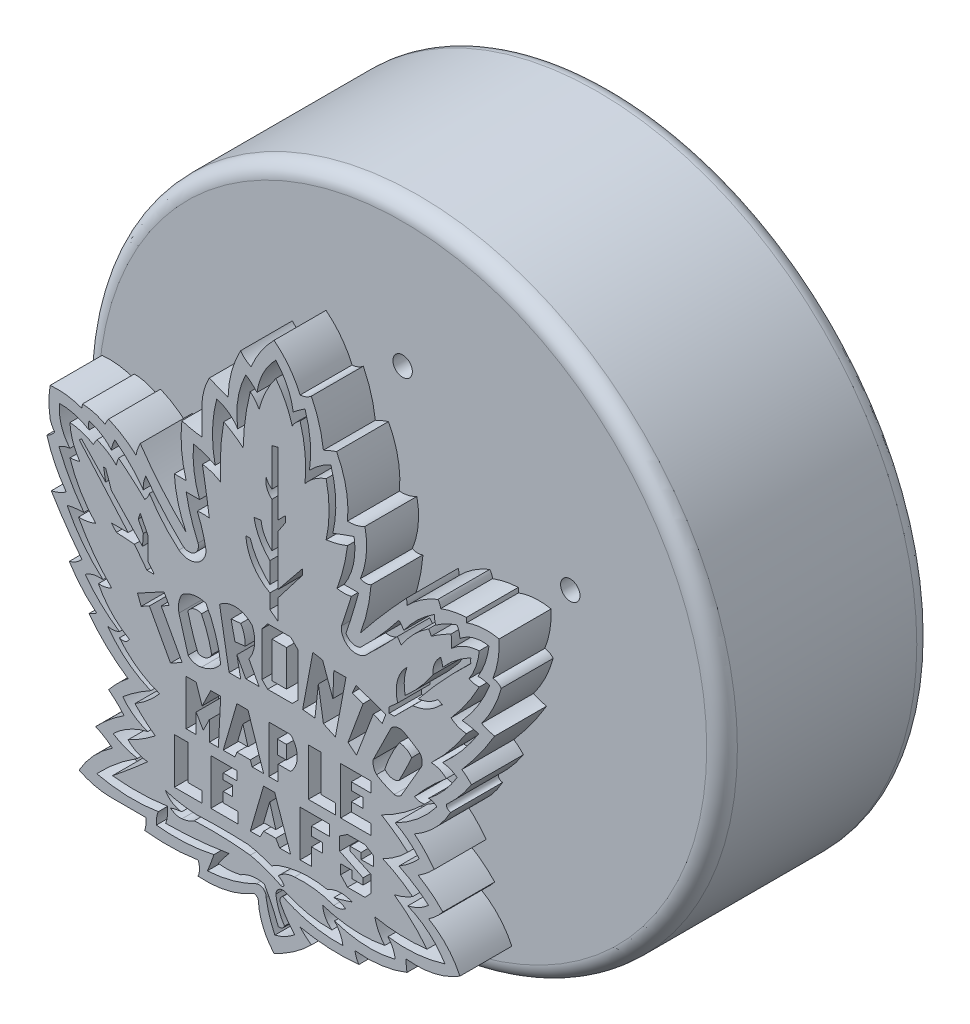
SolidWorks part; units mm, degrees
ref_plane "Front Plane" through (0, 0, 0) normal (0, 0, 1) x (1, 0, 0)
ref_plane "Top Plane" through (0, 0, 0) normal (0, 1, 0) x (1, 0, 0)
ref_plane "Right Plane" through (0, 0, 0) normal (1, 0, 0) x (0, 0, -1)
sketch "Sketch1" plane through (0, 0, 0) normal (0, 0, 1) x (1, 0, 0)
  line L0 (34.5, 121.5) -> (172.5, 121.5) construction
  line L1 (6.3057, 68.3336) -> (15.8951, 57.3506)
  line L6 (30.3167, 86.1583) -> (30.3167, 80.7546)
  line L7 (27.2525, 71.8253) -> (24.9367, 71.8253)
  line L8 (6.9514, 74.6669) -> (6.8534, 73.8865)
  line L9 (12.1754, 10.8034) -> (19.3568, 10.8034)
  line L10 (15.8951, 57.3506) -> (12.6238, 57.3506)
  line L11 (12.6238, 57.3506) -> (13.5994, 56.2333)
  line L12 (13.5994, 56.2333) -> (17.1344, 55.9938)
  line L13 (17.1344, 55.9938) -> (19.5676, 52.8135)
  line L14 (19.5676, 52.8135) -> (21.025, 52.8135)
  line L15 (21.025, 52.8135) -> (19.7407, 54.4922)
  line L16 (19.7407, 54.4922) -> (19.7407, 58.8908)
  line L17 (19.7407, 58.8908) -> (18.2642, 61.8099)
  line L18 (18.2642, 61.8099) -> (17.8765, 60.6287)
  line L19 (17.8765, 60.6287) -> (18.8654, 58.6737)
  line L20 (18.8654, 58.6737) -> (18.7132, 56.4273)
  line L21 (18.7132, 56.4273) -> (12.6238, 62.8421)
  line L22 (12.6238, 62.8421) -> (11.5036, 66.0747)
  line L25 (11.5036, 63.7081) -> (6.8096, 68.653)
  line L26 (6.8096, 68.653) -> (6.3057, 68.3336)
  line L27 (11.5036, 63.7081) -> (11.1004, 66.0747)
  line L28 (11.1004, 66.0747) -> (11.5036, 66.0747)
  line L29 (44.0339, 86.1583) -> (45.2677, 86.4828)
  line L30 (45.2677, 86.4828) -> (45.2677, 74.1922)
  line L31 (45.2677, 74.1922) -> (46.7323, 75.6568)
  line L32 (46.7323, 75.6568) -> (46.7323, 74.5052)
  line L33 (46.7323, 74.5052) -> (45.2677, 72.2648)
  line L34 (45.2677, 72.2648) -> (45.2677, 62.4102)
  line L35 (45.2677, 62.4102) -> (50.0411, 68.3336)
  line L36 (50.0411, 68.3336) -> (50.0411, 67.2036)
  line L37 (50.0411, 67.2036) -> (45.2677, 61.0086)
  line L38 (45.2677, 61.0086) -> (45.2677, 56.9127)
  line L39 (45.2677, 56.9127) -> (43.6367, 58.1694)
  line L40 (43.6367, 58.1694) -> (43.6367, 61.0086)
  line L41 (38.9245, 68.3336) -> (39.7941, 68.3336)
  line L42 (40.5155, 72.2648) -> (41.9224, 72.4343)
  line L43 (41.9224, 72.4343) -> (41.9224, 72.3332)
  line L44 (43.6367, 66.4741) -> (43.6367, 62.4102)
  line L45 (44.0339, 78.7841) -> (44.0339, 86.1583)
  line L46 (44.0339, 68.3336) -> (44.0339, 77.0681)
  line L48 (66.9786, 53.365) -> (66.9786, 52.2776)
  line L49 (66.9786, 52.2776) -> (67.9755, 52.2776)
  line L50 (67.9755, 52.2776) -> (71.5619, 55.8427)
  line L51 (66.9786, 53.365) -> (68.6517, 54.8561)
  line L52 (76.5056, 59.3605) -> (77.4165, 58.8908)
  line L53 (77.4165, 58.8908) -> (77.0329, 58.6853)
  line L54 (29.874, 69.9206) -> (27.2525, 69.9206)
  line L55 (17.7325, 48.0078) -> (22.922, 50.8265)
  line L56 (22.922, 50.8265) -> (23.9165, 48.9955)
  line L57 (23.9165, 48.9955) -> (22.3701, 48.1556)
  line L58 (22.3701, 48.1556) -> (26.4629, 40.6203)
  line L59 (26.4629, 40.6203) -> (24.1884, 39.3849)
  line L60 (24.1884, 39.3849) -> (20.0547, 46.9954)
  line L61 (20.0547, 46.9954) -> (18.4461, 46.1217)
  line L62 (18.4461, 46.1217) -> (17.7325, 48.0078)
  line L63 (42.0881, 54.1273) -> (42.0881, 45.5535)
  line L64 (42.0881, 45.5535) -> (43.1911, 44.4505)
  line L65 (43.1911, 44.4505) -> (48.0086, 44.4505)
  line L66 (48.0086, 44.4505) -> (49.1116, 45.5535)
  line L67 (49.1116, 45.5535) -> (49.1116, 54.1273)
  line L68 (49.1116, 54.1273) -> (47.6913, 55.5476)
  line L69 (47.6913, 55.5476) -> (43.1911, 55.5476)
  line L70 (43.1911, 55.5476) -> (42.0881, 54.1273)
  line L71 (44.0339, 53.365) -> (46.8868, 53.365)
  line L72 (46.8868, 53.365) -> (46.8868, 46.3139)
  line L73 (46.8868, 46.3139) -> (44.0339, 46.3139)
  line L74 (44.0339, 46.3139) -> (44.0339, 53.365)
  line L75 (33.7917, 54.1273) -> (35.6496, 43.498)
  line L76 (35.6496, 43.498) -> (37.933, 43.498)
  line L77 (37.933, 43.498) -> (37.1838, 47.2971)
  line L78 (37.1838, 47.2971) -> (38.9245, 44.0735)
  line L79 (38.9245, 44.0735) -> (41.5213, 44.0735)
  line L80 (41.5213, 44.0735) -> (39.5306, 47.7599)
  line L81 (36.0392, 52.7859) -> (36.7945, 49.3156)
  line L82 (36.7945, 49.3156) -> (38.7916, 49.5311)
  line L83 (36.0392, 52.7859) -> (37.933, 52.9837)
  line L84 (25.8383, 48.6827) -> (27.6283, 42.4266)
  line L85 (50.0411, 44.4505) -> (52.0362, 55.1267)
  line L86 (52.0362, 55.1267) -> (53.9533, 54.7684)
  line L87 (53.9533, 54.7684) -> (55.9534, 49.2355)
  line L88 (55.9534, 49.2355) -> (56.144, 54.1273)
  line L89 (56.144, 54.1273) -> (58.5251, 54.1273)
  line L90 (58.5251, 54.1273) -> (56.4417, 42.9794)
  line L91 (56.4417, 42.9794) -> (54.1026, 44.0735)
  line L92 (54.1026, 44.0735) -> (53.1196, 50.3069)
  line L93 (53.1196, 50.3069) -> (52.4464, 44.1881)
  line L94 (52.4464, 44.1881) -> (50.0411, 44.4505)
  line L96 (66.3288, 51.7517) -> (65.6176, 49.8908)
  line L97 (65.6176, 49.8908) -> (63.8591, 50.5629)
  line L98 (63.8591, 50.5629) -> (60.5679, 41.9509)
  line L99 (60.5679, 41.9509) -> (58.9206, 43.3234)
  line L100 (58.9206, 43.3234) -> (61.8601, 51.3268)
  line L101 (61.8601, 51.3268) -> (59.7442, 52.1039)
  line L103 (59.7442, 52.1039) -> (60.5123, 53.7569)
  line L104 (60.5123, 53.7569) -> (66.3288, 51.7517)
  line L105 (63.8591, 42.8783) -> (67.3185, 49.8908)
  line L106 (69.358, 39.5777) -> (73.2604, 46.3139)
  line L107 (27.2525, 29.7743) -> (27.2525, 38.6676)
  line L108 (27.2525, 38.6676) -> (29.1958, 38.6676)
  line L109 (29.1958, 38.6676) -> (30.3678, 35.2087)
  line L110 (30.3678, 35.2087) -> (32.0759, 38.6676)
  line L111 (32.0759, 38.6676) -> (34.0127, 38.6676)
  line L112 (34.0127, 38.6676) -> (33.5534, 29.7743)
  line L113 (33.5534, 29.7743) -> (31.7771, 29.7743)
  line L114 (31.7771, 29.7743) -> (31.7771, 33.586)
  line L115 (31.7771, 33.586) -> (30.6072, 31.2168)
  line L116 (30.6072, 31.2168) -> (29.1958, 33.586)
  line L117 (29.1958, 33.586) -> (29.1958, 29.7743)
  line L118 (29.1958, 29.7743) -> (27.2525, 29.7743)
  line L119 (34.4991, 29.7743) -> (36.7945, 29.7743)
  line L120 (36.7945, 29.7743) -> (37.1838, 30.7878)
  line L121 (37.1838, 30.7878) -> (39.7941, 30.7878)
  line L122 (39.7941, 30.7878) -> (40.1678, 29.7743)
  line L123 (40.1678, 29.7743) -> (42.3991, 29.7743)
  line L124 (42.3991, 29.7743) -> (39.3473, 39.0131)
  line L125 (39.3473, 39.0131) -> (37.1838, 39.0131)
  line L126 (37.1838, 39.0131) -> (34.4991, 29.7743)
  line L127 (37.3474, 32.7715) -> (39.3473, 32.7715)
  line L128 (39.3473, 32.7715) -> (38.3474, 36.1374)
  line L129 (38.3474, 36.1374) -> (37.3474, 32.7715)
  line L130 (43.4149, 29.7743) -> (43.4149, 39.0131)
  line L131 (43.4149, 39.0131) -> (47.6913, 39.0131)
  line L132 (43.4149, 29.7743) -> (45.2399, 29.7743)
  line L133 (45.2399, 29.7743) -> (45.2399, 32.7715)
  line L134 (45.2399, 32.7715) -> (47.6913, 32.7715)
  line L135 (51.1553, 39.0131) -> (53.5887, 39.0131)
  line L136 (45.0765, 36.9598) -> (46.8868, 36.9598)
  line L137 (45.0765, 36.9598) -> (45.0765, 34.2952)
  line L138 (45.0765, 34.2952) -> (46.8868, 34.2952)
  line L139 (46.8868, 36.9598) -> (46.8868, 34.2952)
  line L140 (53.5887, 39.0131) -> (53.5887, 31.8324)
  line L141 (53.5887, 31.8324) -> (56.4417, 31.8324)
  line L145 (51.1553, 39.0131) -> (51.1553, 29.7743)
  line L146 (51.1553, 29.7743) -> (56.4417, 29.7743)
  line L147 (56.4417, 29.7743) -> (56.4417, 31.8324)
  line L148 (57.4755, 29.7743) -> (63.4335, 29.7743)
  line L149 (63.4335, 29.7743) -> (63.4335, 31.8324)
  line L150 (63.4335, 31.8324) -> (59.5649, 31.8324)
  line L151 (59.5649, 31.8324) -> (59.5649, 33.586)
  line L152 (59.5649, 33.586) -> (61.8601, 33.586)
  line L153 (61.8601, 33.586) -> (61.8601, 35.4618)
  line L154 (61.8601, 35.4618) -> (59.5649, 35.4618)
  line L155 (59.5649, 35.4618) -> (59.5649, 36.9598)
  line L156 (59.5649, 36.9598) -> (63.4335, 36.9598)
  line L157 (63.4335, 36.9598) -> (63.4335, 39.0131)
  line L158 (63.4335, 39.0131) -> (57.4755, 39.0131)
  line L159 (57.4755, 39.0131) -> (57.4755, 29.7743)
  line L160 (24.9367, 27.6583) -> (27.6283, 27.6583)
  line L161 (27.6283, 27.6583) -> (27.6283, 20.8444)
  line L162 (27.6283, 20.8444) -> (30.3678, 20.8444)
  line L163 (30.3678, 20.8444) -> (30.3678, 18.7141)
  line L164 (30.3678, 18.7141) -> (24.9367, 18.7141)
  line L165 (24.9367, 18.7141) -> (24.9367, 27.6583)
  line L166 (32.0759, 27.6583) -> (32.0759, 18.7141)
  line L167 (32.0759, 18.7141) -> (37.3474, 18.7141)
  line L168 (37.3474, 18.7141) -> (37.3474, 20.8444)
  line L169 (37.3474, 20.8444) -> (34.4991, 20.8444)
  line L170 (34.4991, 20.8444) -> (34.4991, 22.8011)
  line L171 (34.4991, 22.8011) -> (36.3392, 22.8011)
  line L172 (36.3392, 22.8011) -> (36.3392, 24.7422)
  line L173 (36.3392, 24.7422) -> (34.4991, 24.7422)
  line L174 (34.4991, 24.7422) -> (34.4991, 25.9294)
  line L175 (34.4991, 25.9294) -> (37.1838, 25.9294)
  line L176 (37.1838, 25.9294) -> (37.1838, 27.6583)
  line L177 (37.1838, 27.6583) -> (32.0759, 27.6583)
  line L178 (39.7941, 18.7141) -> (41.7277, 18.7141)
  line L179 (41.7277, 18.7141) -> (42.3991, 19.9957)
  line L180 (42.3991, 19.9957) -> (44.7952, 19.9957)
  line L181 (44.7952, 19.9957) -> (45.5443, 18.7141)
  line L182 (45.5443, 18.7141) -> (47.6913, 18.7141)
  line L183 (44.5704, 27.6583) -> (47.6913, 18.7141)
  line L184 (39.7941, 18.7141) -> (42.3991, 27.6583)
  line L185 (42.3991, 27.6583) -> (44.5704, 27.6583)
  line L186 (42.3991, 21.453) -> (44.7952, 21.453)
  line L187 (44.7952, 21.453) -> (43.5971, 25.5575)
  line L188 (43.5971, 25.5575) -> (42.3991, 21.453)
  line L189 (49.5479, 18.7141) -> (49.5479, 27.6583)
  line L190 (49.5479, 27.6583) -> (55.2493, 27.6583)
  line L191 (55.2493, 27.6583) -> (55.2493, 25.5575)
  line L192 (55.2493, 25.5575) -> (51.7544, 25.5575)
  line L193 (51.7544, 25.5575) -> (51.7544, 23.847)
  line L194 (51.7544, 23.847) -> (53.9533, 23.847)
  line L195 (53.9533, 23.847) -> (53.9533, 22.028)
  line L196 (53.9533, 22.028) -> (51.7544, 22.028)
  line L197 (51.7544, 22.028) -> (51.7544, 18.7141)
  line L198 (51.7544, 18.7141) -> (49.5479, 18.7141)
  line L199 (57.4755, 22.028) -> (59.6905, 22.028)
  line L200 (61.4891, 24.7422) -> (63.8591, 24.7422)
  line L201 (58.8218, 27.6583) -> (62.2386, 27.6583)
  line L202 (57.2969, 24.067) -> (57.2969, 26.6528)
  line L203 (58.8218, 18.7141) -> (62.2386, 18.7141)
  line L204 (63.4335, 23.1835) -> (63.4335, 19.9957)
  line L205 (63.8591, 24.7422) -> (63.8591, 26.6528)
  line L206 (57.4755, 22.028) -> (57.4755, 20.164)
  line L207 (57.4755, 20.164) -> (58.8218, 18.7141)
  line L208 (62.2386, 18.7141) -> (63.4335, 19.9957)
  line L209 (57.2969, 26.6528) -> (58.8218, 27.6583)
  line L210 (62.2386, 27.6583) -> (63.8591, 26.6528)
  line L211 (57.2969, 24.067) -> (61.8601, 21.8277)
  line L212 (61.8601, 21.8277) -> (61.8601, 20.5939)
  line L213 (61.8601, 20.5939) -> (59.6905, 20.5939)
  line L214 (59.6905, 20.5939) -> (59.6905, 22.028)
  line L215 (61.4891, 24.7422) -> (61.4652, 25.9294)
  line L216 (61.4652, 25.9294) -> (59.3097, 25.9294)
  line L219 (63.4335, 23.1835) -> (59.3097, 25.1115)
  line L220 (59.3097, 25.1115) -> (59.3097, 25.9294)
  arc A0 (39.953, 97.4839) -> (44.45, 104.2073) centre (59.6905, 89.1481) cw
  arc A1 (37.8969, 99.1631) -> (39.953, 97.4839) centre (41.9224, 101.9937) ccw
  arc A2 (37.8969, 99.1631) -> (35.4553, 90.046) centre (55.567, 89.5455) ccw
  arc A3 (35.4553, 90.046) -> (31.7771, 91.4752) centre (63.8591, 168.5955) cw
  arc A4 (31.7771, 91.4752) -> (30.3167, 86.1583) centre (42.5693, 85.652) ccw
  arc A5 (26.4126, 81.5637) -> (30.3167, 80.7546) centre (32.5268, 101.2426) ccw
  arc A6 (26.4126, 81.5637) -> (27.2525, 71.8253) centre (51.0633, 78.7841) ccw
  arc A7 (24.9367, 71.8253) -> (27.2525, 63.058) centre (47.3507, 73.056) ccw
  arc A8 (18.2642, 73.6371) -> (27.2525, 63.058) centre (72.867, 110.9209) ccw
  arc A9 (18.2642, 73.6371) -> (17.4501, 71.228) centre (25.2907, 69.9206) ccw
  arc A10 (12.0805, 74.6669) -> (17.4501, 71.228) centre (4.7765, 57.3506) cw
  arc A11 (12.0805, 74.6669) -> (11.3954, 73.4241) centre (15.8951, 71.7539) ccw
  arc A12 (6.9514, 74.6669) -> (11.3954, 73.4241) centre (6.8096, 65.5926) cw
  arc A13 (0.6356, 74.6669) -> (6.8534, 73.8865) centre (2.0793, 61.0086) cw
  arc A14 (0.6356, 74.6669) -> (0.6356, 68.9794) centre (18.0812, 71.8231) ccw
  arc A15 (0.6356, 68.9794) -> (1.5259, 67.2036) centre (5.7551, 70.4349) ccw
  arc A16 (1.5259, 67.2036) -> (0, 65.9359) centre (-1.3367, 69.0971) cw
  arc A17 (0, 65.9359) -> (3.7896, 58.1694) centre (24.1015, 72.8882) ccw
  arc A18 (3.7896, 58.1694) -> (0.8565, 56.9127) centre (-0.9293, 65.1323) cw
  arc A19 (0.8565, 56.9127) -> (6.8534, 48.2966) centre (72.2331, 100.1966) ccw
  arc A20 (4.382, 46.7197) -> (6.8534, 48.2966) centre (3.1638, 51.3542) ccw
  arc A21 (4.382, 46.7197) -> (9.7464, 40.6203) centre (24.3706, 58.8908) ccw
  arc A22 (8.2378, 39.8005) -> (9.7464, 40.6203) centre (4.518, 48.4431) ccw
  arc A23 (8.2378, 39.8005) -> (15.8951, 32.601) centre (33.1958, 58.6737) ccw
  arc A24 (12.0805, 28.814) -> (15.8951, 32.601) centre (29.9388, 14.6403) cw
  arc A25 (12.0805, 28.814) -> (15.0982, 25.9294) centre (0.9087, 14.1061) cw
  arc A26 (15.0982, 25.9294) -> (9.539, 21.2972) centre (30.9827, 1.214) ccw
  arc A27 (9.539, 21.2972) -> (12.8259, 19.2826) centre (4.6564, 9.6427) cw
  arc A28 (6.3057, 12.3095) -> (12.8259, 19.2826) centre (24.2625, 2.0539) cw
  arc A29 (6.3057, 12.3095) -> (12.1754, 10.8034) centre (12.6238, 24.7422) ccw
  arc A30 (19.3568, 10.8034) -> (19.1163, 8.4963) centre (14.9335, 10.0985) cw
  arc A31 (19.1163, 8.4963) -> (29.5823, 8.709) centre (23.5846, 46.2274) ccw
  arc A32 (29.5823, 8.709) -> (29.5823, 5.9712) centre (26.3569, 7.3401) cw
  arc A33 (29.5823, 5.9712) -> (40.5155, 8.4963) centre (31.1057, 24.307) ccw
  arc A34 (44.45, 104.2073) -> (49.5479, 97.4839) centre (34.0638, 91.0379) cw
  arc A35 (49.5479, 97.4839) -> (51.7544, 98.4025) centre (49.2697, 101.2615) ccw
  arc A36 (51.7544, 98.4025) -> (54.1026, 90.4118) centre (29.874, 87.6322) cw
  arc A37 (54.1026, 90.4118) -> (56.6792, 91.4752) centre (64.492, 68.8911) cw
  arc A38 (56.6792, 91.4752) -> (58.8218, 80.7546) centre (39.7941, 82.5261) cw
  arc A39 (58.8218, 80.7546) -> (62.2386, 81.5637) centre (59.177, 86.8735) ccw
  arc A40 (62.2386, 81.5637) -> (61.3432, 72.2648) centre (46.7323, 78.3642) cw
  arc A41 (61.3432, 72.2648) -> (63.4335, 72.2648) centre (62.3883, 74.5052) ccw
  arc A42 (63.4335, 72.2648) -> (61.3432, 63.058) centre (30.4249, 74.9185) cw
  arc A43 (61.3432, 63.058) -> (70.3121, 73.4241) centre (191.3667, -40.3773) cw
  arc A44 (70.3121, 73.4241) -> (70.4669, 72.2648) centre (68.2918, 72.5643) cw
  arc A45 (70.4669, 72.2648) -> (76.5056, 76.3413) centre (82.9428, 60.2945) cw
  arc A46 (76.5056, 76.3413) -> (77.0329, 75.0266) centre (74.6899, 74.8498) cw
  arc A47 (77.0329, 75.0266) -> (82.0829, 76.0779) centre (82.8066, 59.947) cw
  arc A48 (82.0829, 76.0779) -> (82.1237, 75.169) centre (74.3776, 75.2768) cw
  arc A49 (82.1237, 75.169) -> (88.49, 75.6241) centre (86.1081, 64.1877) cw
  arc A50 (88.49, 75.6241) -> (87.2683, 68.3336) centre (71.03, 74.8023) cw
  arc A51 (87.2683, 68.3336) -> (88.9, 67.4547) centre (87.1042, 66.0747) cw
  arc A52 (85.0576, 59.5877) -> (88.9, 67.4547) centre (66.3288, 73.6069) ccw
  arc A53 (85.0576, 59.5877) -> (87.6244, 58.7299) centre (89.2132, 67.7531) ccw
  arc A54 (81.198, 49.8492) -> (87.6244, 58.7299) centre (34.0127, 90.7599) ccw
  arc A55 (81.198, 49.8492) -> (83.0778, 48.2194) centre (75.7967, 41.7206) cw
  arc A56 (78.1618, 42.4266) -> (83.0778, 48.2194) centre (58.9206, 63.7376) ccw
  arc A57 (78.1618, 42.4266) -> (79.005, 41.4927) centre (79.0503, 42.3812) ccw
  arc A58 (79.005, 41.4927) -> (71.9204, 34.2952) centre (63.0636, 50.0984) cw
  arc A59 (71.9204, 34.2952) -> (75.7967, 30.2227) centre (58.1473, 17.3044) cw
  arc A60 (72.6556, 27.6583) -> (75.7967, 30.2227) centre (62.8474, 42.8783) ccw
  arc A61 (72.6556, 27.6583) -> (77.4679, 23.847) centre (61.9836, 9.2398) cw
  arc A62 (74.6899, 21.2972) -> (77.4679, 23.847) centre (68.1498, 31.2112) ccw
  arc A63 (74.6899, 21.2972) -> (80.8123, 14.6403) centre (67.3185, 8.3739) cw
  arc A64 (70.3121, 12.3095) -> (80.8123, 14.6403) centre (72.2864, 28.2321) ccw
  arc A65 (60.2753, 8.709) -> (70.4669, 10.0985) centre (62.6359, 29.4655) ccw
  arc A66 (70.3121, 12.3095) -> (70.4669, 10.0985) centre (78.1512, 11.7475) ccw
  arc A67 (60.2753, 8.709) -> (61.0619, 6.7442) centre (64.4973, 9.2592) ccw
  arc A68 (49.5479, 7.3401) -> (61.0619, 6.7442) centre (57.1649, 42.9794) ccw
  arc A69 (49.5479, 7.3401) -> (51.7544, 5.4046) centre (58.4524, 15.266) ccw
  arc A70 (40.5155, 8.4963) -> (41.376, 7.6769) centre (40.536, 7.6564) cw
  arc A71 (41.376, 7.6769) -> (44.45, 0.3121) centre (53.5887, 8.4505) ccw
  arc A72 (44.45, 0.3121) -> (51.7544, 5.4046) centre (33.5534, 23.7265) ccw
  arc A73 (43.6367, 61.0086) -> (38.9245, 68.3336) centre (48.0086, 68.9992) cw
  arc A74 (39.7941, 68.3336) -> (43.6367, 62.4102) centre (52.4464, 72.3332) ccw
  arc A75 (40.5155, 72.2648) -> (43.6367, 66.4741) centre (51.1915, 74.2827) ccw
  arc A76 (41.9224, 72.3332) -> (44.0339, 68.3336) centre (48.4459, 73.22) ccw
  arc A77 (42.8971, 80.3015) -> (44.0339, 77.0681) centre (46.1509, 79.6289) ccw
  arc A78 (42.8971, 80.3015) -> (44.0339, 78.7841) centre (45.733, 81.2416) ccw
  arc A79 (68.6517, 54.8561) -> (70.4669, 61.8099) centre (75.1999, 56.8606) cw
  arc A80 (70.101, 56.8606) -> (70.4669, 61.8099) centre (79.0769, 58.6853) cw
  arc A81 (70.101, 56.8606) -> (75.5187, 63.058) centre (50.8202, 79.1822) ccw
  arc A82 (75.5187, 63.058) -> (77.0329, 66.7956) centre (80.2613, 63.3121) cw
  arc A83 (77.0329, 66.7956) -> (77.4165, 65.2735) centre (74.1185, 65.2517) cw
  arc A84 (77.4165, 65.2735) -> (82.9428, 69.6636) centre (91.8679, 52.7553) cw
  arc A85 (82.9428, 69.6636) -> (82.9428, 68.653) centre (91.7697, 69.1583) ccw
  arc A86 (82.9428, 68.653) -> (72.6556, 57.5455) centre (159.5754, -12.6376) ccw
  arc A87 (71.5619, 55.8427) -> (77.0329, 58.6853) centre (70.4486, 64.6718) ccw
  arc A88 (72.6556, 57.5455) -> (76.5056, 59.3605) centre (71.7707, 64.4135) ccw
  arc A89 (23.1917, 17.3044) -> (29.1958, 16.243) centre (30.2497, 39.7188) ccw
  arc A90 (23.1917, 17.3044) -> (26.3569, 15.266) centre (26.7477, 19.3496) ccw
  arc A91 (24.2011, 14.8338) -> (26.3569, 15.266) centre (26.6884, 8.0199) cw
  arc A92 (24.2011, 14.8338) -> (26.4126, 14.1061) centre (26.15, 17.0321) ccw
  arc A93 (26.4126, 14.1061) -> (28.8466, 14.9915) centre (25.8383, 19.4728) ccw
  arc A94 (28.8466, 14.9915) -> (39.7941, 14.6403) centre (32.1233, -53.6633) cw
  arc A95 (39.7941, 14.6403) -> (45.733, 12.4966) centre (34.6999, -8.7709) cw
  arc A96 (45.733, 12.4966) -> (46.4216, 12.84) centre (45.9056, 13.0126) ccw
  arc A97 (45.2677, 13.8729) -> (46.4216, 12.84) centre (44.0158, 11.3133) cw
  arc A98 (45.2677, 13.8729) -> (48.4459, 15.266) centre (48.5512, 10.7037) cw
  arc A99 (48.4459, 15.266) -> (56.144, 14.2945) centre (50.1038, -2.5822) cw
  arc A100 (56.144, 14.2945) -> (58.4524, 14.8619) centre (56.6713, 17.1288) ccw
  arc A101 (58.4524, 14.8619) -> (56.144, 15.6253) centre (56.2765, 12.1538) ccw
  arc A102 (56.144, 15.6253) -> (59.6905, 16.6676) centre (49.2746, 45.5535) ccw
  arc A103 (59.6905, 16.6676) -> (54.8834, 16.361) centre (57.5817, 11.8918) ccw
  arc A104 (45.2399, 15.6151) -> (54.8834, 16.361) centre (51.3871, -1.1493) cw
  arc A105 (45.2399, 15.6151) -> (44.0158, 14.8618) centre (46.484, 12.2222) ccw
  arc A106 (44.0158, 14.8618) -> (39.3473, 16.243) centre (36.0392, -3.5187) ccw
  arc A107 (29.1958, 16.243) -> (39.3473, 16.243) centre (34.2715, -88.6983) cw
  arc A108 (41.1071, 93.6951) -> (44.7952, 101.0181) centre (54.0654, 91.7591) cw
  arc A109 (41.1071, 93.6951) -> (38.9245, 95.6058) centre (33.2426, 86.9131) ccw
  arc A110 (38.9245, 95.6058) -> (37.3474, 85.652) centre (53.9533, 88.1227) ccw
  arc A111 (37.3474, 85.652) -> (33.2426, 88.6762) centre (31.1465, 81.5333) ccw
  arc A112 (33.2426, 88.6762) -> (32.9284, 77.2581) centre (56.9087, 82.3117) ccw
  arc A113 (29.874, 69.9206) -> (28.6937, 78.7841) centre (48.7818, 76.9488) cw
  arc A114 (28.6937, 78.7841) -> (32.9284, 77.2581) centre (25.5519, 63.4266) cw
  arc A115 (26.4126, 60.6287) -> (29.5823, 62.4102) centre (27.7758, 61.9138) ccw
  arc A116 (29.5823, 62.4102) -> (27.2525, 69.9206) centre (58.5251, 75.5051) cw
  arc A117 (26.4126, 60.6287) -> (19.3568, 68.653) centre (70.7595, 106.7371) cw
  arc A118 (18.8654, 66.0747) -> (19.3568, 68.653) centre (23.8409, 66.4623) cw
  arc A119 (18.8654, 66.0747) -> (13.313, 71.7539) centre (-1.6958, 51.5262) ccw
  arc A120 (13.313, 71.7539) -> (12.6238, 69.6636) centre (18.3307, 68.9409) ccw
  arc A121 (12.6238, 69.6636) -> (8.2378, 72.4343) centre (6.1876, 64.3318) ccw
  arc A122 (8.2378, 72.4343) -> (8.2378, 70.8974) centre (12.1478, 71.6658) ccw
  arc A123 (8.2378, 70.8974) -> (2.5118, 72.525) centre (2.5997, 61.948) ccw
  arc A124 (2.5118, 72.525) -> (4.518, 65.9359) centre (10.826, 71.4564) ccw
  arc A125 (2.3637, 65.1323) -> (4.518, 65.9359) centre (4.9076, 61.6023) cw
  arc A126 (2.3637, 65.1323) -> (7.2499, 56.4273) centre (37.933, 79.3738) ccw
  arc A127 (3.9571, 55.9938) -> (7.2499, 56.4273) centre (7.4699, 42.0351) cw
  arc A128 (3.9571, 55.9938) -> (10.9871, 46.9175) centre (30.3396, 69.1676) ccw
  arc A129 (7.4699, 46.0561) -> (10.9871, 46.9175) centre (10.3393, 41.9509) cw
  arc A130 (7.4699, 46.0561) -> (14.2015, 39.7188) centre (29.4197, 62.6275) ccw
  arc A131 (14.2015, 39.7188) -> (11.919, 39.4664) centre (12.6902, 42.9388) cw
  arc A132 (11.919, 39.4664) -> (20.3138, 32.7715) centre (27.6283, 50.5537) ccw
  arc A133 (14.8465, 29.0375) -> (20.3138, 32.7715) centre (38.3993, 0.4212) cw
  arc A134 (14.8465, 29.0375) -> (19.7407, 25.5575) centre (22.6986, 34.8989) ccw
  arc A135 (12.9629, 21.8277) -> (19.7407, 25.5575) centre (23.2443, 11.1673) cw
  arc A136 (12.9629, 21.8277) -> (17.7325, 19.9957) centre (19.7074, 32.262) ccw
  arc A137 (9.7464, 13.4212) -> (17.7325, 19.9957) centre (39.8196, -14.9717) cw
  arc A138 (9.7464, 13.4212) -> (21.8035, 13.0126) centre (16.8207, 44.0735) ccw
  arc A139 (21.8035, 13.0126) -> (21.4197, 10.539) centre (26.5448, 11.0104) ccw
  arc A140 (21.4197, 10.539) -> (32.6724, 11.1673) centre (25.1455, 44.89) ccw
  arc A141 (32.6724, 11.1673) -> (31.397, 7.7771) centre (-3.4135, 22.8077) cw
  arc A142 (31.397, 7.7771) -> (40.9974, 10.3912) centre (29.8809, 32.2813) ccw
  arc A143 (40.9974, 10.3912) -> (42.8971, 8.9883) centre (41.5213, 9.1129) cw
  arc A144 (42.8971, 8.9883) -> (44.6005, 3.4896) centre (62.7339, 12.1204) ccw
  arc A145 (45.733, 9.457) -> (48.4826, 5.4981) centre (60.4844, 16.768) ccw
  arc A146 (44.6005, 3.4896) -> (48.4826, 5.4981) centre (42.0881, 13.1016) ccw
  arc A147 (46.1509, 10.8034) -> (57.9289, 8.3739) centre (56.8939, 33.1202) ccw
  arc A148 (57.9289, 8.3739) -> (56.2765, 11.7475) centre (51.8457, 7.4858) ccw
  arc A149 (56.2765, 11.7475) -> (68.1498, 11.1673) centre (63.1787, 31.2168) ccw
  arc A150 (66.7337, 14.2945) -> (68.1498, 11.1673) centre (62.6015, 10.5391) cw
  arc A151 (66.7337, 14.2945) -> (77.8863, 15.266) centre (70.1991, 39.0131) ccw
  arc A152 (77.8863, 15.266) -> (70.6118, 21.453) centre (64.7964, 7.2454) ccw
  arc A153 (70.6118, 21.453) -> (74.6899, 23.5928) centre (68.5725, 30.2957) ccw
  arc A154 (68.8841, 27.3392) -> (74.6899, 23.5928) centre (57.1113, 2.7232) cw
  arc A155 (68.8841, 27.3392) -> (72.867, 30.542) centre (59.3097, 43.3234) ccw
  arc A156 (72.867, 30.542) -> (68.1498, 34.2952) centre (60.9825, 20.4457) ccw
  arc A157 (68.1498, 34.2952) -> (76.2947, 41.065) centre (57.7212, 55.1267) ccw
  arc A158 (76.2947, 41.065) -> (74.6899, 41.7206) centre (74.7507, 39.5777) ccw
  arc A159 (74.6899, 41.7206) -> (80.2613, 48.0078) centre (60.1125, 60.2507) ccw
  arc A160 (80.2613, 48.0078) -> (77.4165, 49.1402) centre (77.093, 44.1881) ccw
  arc A161 (77.4165, 49.1402) -> (84.4931, 57.5455) centre (50.746, 78.7761) ccw
  arc A162 (84.4931, 57.5455) -> (81.2458, 58.1694) centre (80.0337, 43.097) ccw
  arc A163 (81.2458, 58.1694) -> (86.6347, 66.7956) centre (60.763, 76.9619) ccw
  arc A164 (86.6347, 66.7956) -> (84.3381, 67.2036) centre (84.6037, 62.0315) ccw
  arc A165 (84.3381, 67.2036) -> (86.4969, 73.4241) centre (71.2291, 75.2379) ccw
  arc A166 (86.4969, 73.4241) -> (80.8123, 71.8253) centre (85.2527, 66.9426) ccw
  arc A167 (80.8123, 71.8253) -> (80.2613, 73.8865) centre (76.4334, 71.7591) ccw
  arc A168 (80.2613, 73.8865) -> (76.0726, 71.7591) centre (85.252, 58.8727) ccw
  arc A169 (69.8401, 67.7531) -> (75.7967, 73.4241) centre (87.7087, 54.9485) cw
  arc A170 (75.7967, 73.4241) -> (76.0726, 71.7591) centre (81.517, 73.5163) ccw
  arc A171 (61.3432, 60.6287) -> (68.8841, 68.9992) centre (11.0265, 113.5405) ccw
  arc A172 (68.8841, 68.9992) -> (69.8401, 67.7531) centre (64.9916, 65.023) cw
  arc A173 (61.3432, 60.6287) -> (58.5251, 61.6023) centre (60.4209, 62.5246) cw
  arc A174 (58.5251, 61.6023) -> (60.9825, 69.6636) centre (-61.6421, 102.6406) ccw
  arc A175 (58.1473, 69.6636) -> (60.9825, 69.6636) centre (59.5649, 35.4618) cw
  arc A176 (58.1473, 69.6636) -> (60.1125, 78.7841) centre (47.3046, 76.7719) ccw
  arc A177 (55.9534, 77.2581) -> (60.1125, 78.7841) centre (87.9513, -3.5221) cw
  arc A178 (55.9534, 77.2581) -> (55.567, 88.6762) centre (34.6088, 82.2514) ccw
  arc A179 (51.3871, 85.652) -> (55.567, 88.6762) centre (61.4891, 76.0905) cw
  arc A180 (51.3871, 85.652) -> (50.507, 95.6058) centre (29.8741, 88.7655) ccw
  arc A181 (48.2115, 93.9465) -> (50.507, 95.6058) centre (62.7955, 76.1878) cw
  arc A182 (44.7952, 101.0181) -> (48.2115, 93.9465) centre (35.0408, 91.9448) cw
  arc A183 (25.8383, 59.3605) -> (31.1465, 61.9138) centre (27.8279, 62.0187) ccw
  arc A184 (31.1465, 61.9138) -> (29.4197, 67.7531) centre (5.7628, 57.5821) ccw
  arc A185 (29.4197, 67.7531) -> (31.7771, 67.7531) centre (30.5984, 60.7145) cw
  arc A186 (31.7771, 67.7531) -> (30.4249, 76.1878) centre (-160.4124, 41.2679) ccw
  arc A187 (30.4249, 76.1878) -> (34.0127, 74.9185) centre (29.6111, 68.1815) cw
  arc A188 (34.0127, 74.9185) -> (34.6088, 85.4791) centre (78.1275, 77.7258) cw
  arc A189 (34.6088, 85.4791) -> (38.3993, 82.9423) centre (25.6126, 67.9369) cw
  arc A190 (38.3993, 82.9423) -> (39.7941, 93.1818) centre (85.3584, 81.7601) cw
  arc A191 (39.7941, 93.1818) -> (41.5213, 91.0379) centre (34.8581, 87.4376) cw
  arc A192 (41.5213, 91.0379) -> (44.7952, 97.9056) centre (60.1507, 86.3711) cw
  arc A193 (44.7952, 97.9056) -> (48.0086, 91.4752) centre (29.7658, 86.3771) cw
  arc A194 (48.0086, 91.4752) -> (49.5479, 93.093) centre (52.0362, 89.1842) cw
  arc A195 (49.5479, 93.093) -> (50.507, 82.9423) centre (24.2639, 85.5833) cw
  arc A196 (50.507, 82.9423) -> (54.6429, 85.8638) centre (57.637, 77.2369) cw
  arc A197 (54.6429, 85.8638) -> (54.6429, 75.5051) centre (31.7976, 80.6845) cw
  arc A198 (54.6429, 75.5051) -> (58.8218, 76.5945) centre (52.694, 91.5402) ccw
  arc A199 (58.8218, 76.5945) -> (56.7689, 68.3336) centre (22.922, 81.1303) cw
  arc A200 (56.7689, 68.3336) -> (59.5649, 68.3692) centre (58.0809, 75.1066) ccw
  arc A201 (59.5649, 68.3692) -> (57.637, 62.4102) centre (-63.7499, 104.9728) cw
  arc A202 (57.637, 62.4102) -> (62.7955, 60.2507) centre (60.5123, 62.0375) ccw
  arc A203 (62.7955, 60.2507) -> (68.5725, 66.0747) centre (-22.2233, 150.3595) ccw
  arc A204 (68.5725, 66.0747) -> (69.358, 65.023) centre (78.0296, 72.3194) ccw
  arc A205 (69.358, 65.023) -> (74.6899, 70.4349) centre (84.8579, 55.0847) cw
  arc A206 (74.6899, 70.4349) -> (75.1999, 69.442) centre (71.1785, 68.0038) cw
  arc A207 (75.1999, 69.442) -> (79.0769, 71.7591) centre (97.0568, 37.2727) cw
  arc A208 (79.0769, 71.7591) -> (79.1709, 69.3506) centre (69.9032, 70.1953) cw
  arc A209 (79.1709, 69.3506) -> (84.6037, 71.6658) centre (85.132, 62.8941) cw
  arc A210 (82.5945, 65.9359) -> (84.6037, 71.6658) centre (71.9626, 72.8814) ccw
  arc A211 (82.5945, 65.9359) -> (84.6037, 65.5397) centre (84.2717, 69.1487) ccw
  arc A212 (79.0769, 57.5455) -> (84.6037, 65.5397) centre (48.0948, 84.8726) ccw
  arc A213 (79.0769, 57.5455) -> (82.0762, 56.3769) centre (82.3851, 61.603) ccw
  arc A214 (75.1999, 48.0078) -> (82.0762, 56.3769) centre (45.668, 79.2816) ccw
  arc A215 (75.1999, 48.0078) -> (78.1618, 46.7935) centre (75.1825, 43.7458) cw
  arc A216 (71.9204, 40.6203) -> (78.1618, 46.7935) centre (109.5068, 8.8603) cw
  arc A217 (71.9204, 40.6203) -> (73.9221, 40.3537) centre (73.2604, 43.0331) ccw
  arc A218 (65.4717, 34.2952) -> (73.9221, 40.3537) centre (51.1553, 63.1862) ccw
  arc A219 (65.4717, 34.2952) -> (70.6118, 30.542) centre (48.2467, 5.308) cw
  arc A220 (65.7322, 26.9981) -> (70.6118, 30.542) centre (57.4755, 43.498) ccw
  arc A221 (65.7322, 26.9981) -> (71.5619, 23.4874) centre (55.6456, 3.6531) cw
  arc A222 (67.9755, 22.028) -> (71.5619, 23.4874) centre (65.458, 33.3513) ccw
  arc A223 (67.9755, 22.028) -> (74.3776, 15.9884) centre (50.7182, -2.6779) cw
  arc A224 (74.3776, 15.9884) -> (64.1753, 16.361) centre (70.4839, 49.2355) cw
  arc A225 (64.1753, 16.361) -> (66.1205, 12.4966) centre (72.1088, 17.9326) ccw
  arc A226 (53.9533, 13.2435) -> (66.1205, 12.4966) centre (61.4652, 36.1374) ccw
  arc A227 (53.9533, 13.2435) -> (55.7775, 9.96) centre (58.4856, 13.613) ccw
  arc A228 (46.8868, 11.7475) -> (55.7775, 9.96) centre (55.2493, 30.3366) ccw
  arc A229 (44.7952, 10.5391) -> (46.8868, 11.7475) centre (46.2188, 10.4894) cw
  arc A230 (44.7952, 10.5391) -> (46.484, 5.9712) centre (55.4649, 11.8877) ccw
  arc A231 (45.2677, 5.308) -> (46.484, 5.9712) centre (45.5443, 6.2478) ccw
  arc A232 (45.2677, 5.308) -> (42.5693, 11.1073) centre (6.1797, -9.3518) ccw
  arc A233 (42.5693, 11.1073) -> (37.933, 10.3774) centre (41.0724, 5.5258) ccw
  arc A234 (33.5534, 10.0985) -> (35.6496, 12.84) centre (57.5016, -6.0411) cw
  arc A235 (33.5534, 10.0985) -> (37.933, 10.3774) centre (34.9433, 22.8011) ccw
  arc A236 (23.2443, 11.7475) -> (35.6496, 12.84) centre (22.7065, 88.8279) ccw
  arc A237 (23.2443, 11.7475) -> (23.5846, 14.8338) centre (17.0314, 13.9944) ccw
  arc A238 (23.5846, 14.8338) -> (12.8259, 14.6226) centre (17.4038, 55.5476) cw
  arc A239 (12.8259, 14.6226) -> (19.7407, 20.4457) centre (-90.1776, 143.9521) ccw
  arc A240 (19.7407, 20.4457) -> (15.8951, 22.2443) centre (20.0547, 26.1276) cw
  arc A241 (15.8951, 22.2443) -> (21.2181, 25.5575) centre (2.6038, 49.5311) ccw
  arc A242 (21.2181, 25.5575) -> (17.2222, 29.0375) centre (36.3392, 46.9546) cw
  arc A243 (17.2222, 29.0375) -> (22.0774, 33.1202) centre (7.2809, 45.7882) ccw
  arc A244 (22.0774, 33.1202) -> (14.2015, 38.6676) centre (27.5931, 49.3156) cw
  arc A245 (14.2015, 38.6676) -> (16.1175, 39.3849) centre (14.8009, 39.9842) ccw
  arc A246 (16.1175, 39.3849) -> (10.0802, 45.7882) centre (23.9165, 52.7859) cw
  arc A247 (10.0802, 45.7882) -> (12.6902, 46.3139) centre (10.3631, 51.1255) ccw
  arc A248 (12.6902, 46.3139) -> (6.1876, 55.1267) centre (38.2724, 71.9954) cw
  arc A249 (6.1876, 55.1267) -> (9.539, 55.7273) centre (6.4331, 63.4068) ccw
  arc A250 (9.539, 55.7273) -> (4.518, 64.3318) centre (26.0882, 71.1516) cw
  arc A251 (4.518, 64.3318) -> (6.4331, 64.6718) centre (4.0675, 72.4332) ccw
  arc A252 (6.4331, 64.6718) -> (4.518, 70.322) centre (15.2822, 70.8208) cw
  arc A253 (4.518, 70.322) -> (9.1041, 68.856) centre (3.6272, 59.6288) cw
  arc A254 (9.1041, 68.856) -> (9.8032, 70.0337) centre (15.0742, 66.1087) cw
  arc A255 (9.8032, 70.0337) -> (13.5994, 67.5982) centre (6.3922, 60.5408) cw
  arc A256 (13.5994, 67.5982) -> (14.0145, 69.0309) centre (20.9701, 66.2393) cw
  arc A257 (14.0145, 69.0309) -> (19.132, 64.5939) centre (-20.3297, 24.249) cw
  arc A258 (19.132, 64.5939) -> (20.0547, 66.0582) centre (17.3263, 66.7547) ccw
  arc A259 (20.0547, 66.0582) -> (25.8383, 59.3605) centre (44.7191, 81.5107) ccw
  arc A260 (33.7917, 54.1273) -> (40.1678, 53.7569) centre (36.7945, 50.7541) cw
  arc A261 (40.1678, 53.7569) -> (39.5306, 47.7599) centre (34.4991, 51.3268) cw
  arc A262 (37.933, 52.9837) -> (38.7916, 49.5311) centre (32.793, 49.8724) cw
  arc A263 (25.8383, 48.6827) -> (26.4126, 52.1038) centre (30.6443, 49.6347) cw
  arc A264 (26.4126, 52.1038) -> (31.1465, 52.9837) centre (29.5908, 48.1795) cw
  arc A265 (27.6283, 42.4266) -> (30.2497, 41.7206) centre (29.5715, 44.4224) ccw
  arc A266 (30.2497, 41.7206) -> (34.0127, 44.0735) centre (29.2251, 47.5449) ccw
  arc A267 (34.0127, 44.0735) -> (31.1465, 52.9837) centre (9.1132, 40.9799) ccw
  arc A268 (27.5931, 49.8724) -> (30.2497, 50.7541) centre (29.3622, 48.9849) cw
  arc A269 (27.5931, 49.8724) -> (29.5715, 43.7458) centre (71.2489, 60.5873) ccw
  arc A270 (29.5715, 43.7458) -> (32.2441, 44.8257) centre (30.3678, 45.622) ccw
  arc A271 (32.2441, 44.8257) -> (30.2497, 50.7541) centre (9.283, 40.401) ccw
  arc A272 (67.3185, 49.8908) -> (70.1991, 50.3069) centre (68.9668, 48.6586) cw
  arc A273 (73.2604, 46.3139) -> (72.867, 48.6586) centre (71.2422, 47.1807) ccw
  arc A274 (72.867, 48.6586) -> (70.1991, 50.3069) centre (49.1736, 13.2922) ccw
  arc A275 (63.8591, 42.8783) -> (64.492, 40.6203) centre (66.5665, 42.4195) ccw
  arc A276 (64.492, 40.6203) -> (67.9755, 39.0131) centre (71.6257, 51.5035) ccw
  arc A277 (67.9755, 39.0131) -> (69.358, 39.5777) centre (68.1515, 40.5572) ccw
  arc A278 (68.9668, 48.2966) -> (71.3833, 46.9546) centre (68.7199, 45.0054) cw
  arc A279 (66.1205, 42.4195) -> (68.9668, 48.2966) centre (89.6431, 34.6552) cw
  arc A280 (66.1205, 42.4195) -> (68.8841, 41.8274) centre (67.7984, 43.5052) ccw
  arc A281 (68.8841, 41.8274) -> (71.3833, 46.9546) centre (-5.8689, 81.4381) ccw
  arc A282 (47.6913, 39.0131) -> (47.6913, 32.7715) centre (44.5704, 35.8923) cw
  arc A283 (45.733, 9.457) -> (46.1509, 10.8034) centre (46.6152, 9.9213) cw
extrude "Boss-Extrude1" add sketch "Sketch1" along normal blind 6.35 contours A71 A72 A69 A68 A67 A65 A66 A64 A63 A62 A61 A60 A59 A58 A57 A56 A55 A54 A53 A52 A51 A50 A49 A48 A47 A46 A45 A44 A43 A42 A41 A40 A39 A38 A37 A36 A35 A34 A0 A1 A2 A3 A4 L6 A5 A6 L7 A7 A8 A9 A10 | A259 A258 A257 A256 A255 A254 A253 A252 A251 A250 A249 A248 A247 A246 A245 A244 A243 A242 A241 A240 A239 A238 A237 A236 A234 A235 A233 A232 A231 A230 A229 A228 A227 A226 A225 A224 A223 A222 A221 A220 A219 A218 A217 A216 A215 A214 A213 A212 A211 A210 A209 | A270 A271 A268 A269 | A262 L83 L81 L82 | L74 L73 L72 L71 | A280 A281 A278 A279 | L187 L188 L186 | L128 L129 L127 | L139 L136 L137 L138 region at (32.0628, 88.5377, 0) region at (45.4603, 49.8395, 0) region at (37.4843, 51.1508, 0) region at (38.3474, 33.8934, 0) region at (45.9816, 35.6275, 0) region at (43.5971, 22.8212, 0) region at (29.798, 57.923, 0) region at (29.943, 47.2855, 0) region at (68.7209, 44.8155, 0)
sketch "Sketch3" plane through (0, 0, 0) normal (0, 0, -1) x (-1, 0, 0)
  line L0 (-44.6508, 86.3206) -> (-45.1697, 19.3549) construction
  line L1 (-44.0339, 86.1583) -> (-45.2677, 86.4828) construction
  line L2 (-44.7952, 19.9957) -> (-45.5443, 18.7141) construction
  line L3 (5.3073, 85.9334) -> (4.7883, 18.9677)
  line L4 (-94.6088, 86.7077) -> (-95.1278, 19.7421)
  arc A0 (5.3073, 85.9334) -> (-94.6088, 86.7077) centre (-44.6508, 86.3206) ccw
  arc A1 (-95.1278, 19.7421) -> (4.7883, 18.9677) centre (-45.1697, 19.3549) ccw
  point P6 (-44.9102, 52.8377)
extrude "Boss-Extrude2" add sketch "Sketch3" along normal blind 3.81
sketch "Sketch4" plane through (0, 0, 0) normal (0, 0, 1) x (1, 0, 0)
  line L1 (-5.3073, 85.9334) -> (-4.7883, 18.9677)
  line L4 (30.3167, 86.1583) -> (30.3167, 80.7546)
  line L5 (27.2525, 71.8253) -> (24.9367, 71.8253)
  line L6 (6.9514, 74.6669) -> (6.8534, 73.8865)
  line L7 (12.1754, 10.8034) -> (19.3568, 10.8034)
  line L8 (30.3167, 86.1583) -> (30.3167, 80.7546)
  line L9 (27.2525, 71.8253) -> (24.9367, 71.8253)
  line L10 (6.9514, 74.6669) -> (6.8534, 73.8865)
  line L11 (12.1754, 10.8034) -> (19.3568, 10.8034)
  line L14 (-5.3073, 85.9334) -> (-4.7883, 18.9677)
  line L15 (95.1278, 19.7421) -> (94.6088, 86.7077)
  line L16 (95.1278, 19.7421) -> (94.6088, 86.7077)
  arc A2 (94.6088, 86.7077) -> (-5.3073, 85.9334) centre (44.6508, 86.3206) ccw
  arc A6 (94.6088, 86.7077) -> (-5.3073, 85.9334) centre (44.6508, 86.3206) ccw
  arc A8 (-4.7883, 18.9677) -> (95.1278, 19.7421) centre (45.1697, 19.3549) ccw
  arc A9 (-4.7883, 18.9677) -> (95.1278, 19.7421) centre (45.1697, 19.3549) ccw
  arc A73 (41.376, 7.6769) -> (44.45, 0.3121) centre (53.5887, 8.4505) ccw
  arc A74 (44.45, 0.3121) -> (51.7544, 5.4046) centre (33.5534, 23.7265) ccw
  arc A75 (49.5479, 7.3401) -> (51.7544, 5.4046) centre (58.4524, 15.266) ccw
  arc A76 (49.5479, 7.3401) -> (61.0619, 6.7442) centre (57.1649, 42.9794) ccw
  arc A77 (60.2753, 8.709) -> (61.0619, 6.7442) centre (64.4973, 9.2592) ccw
  arc A78 (60.2753, 8.709) -> (70.4669, 10.0985) centre (62.6359, 29.4655) ccw
  arc A79 (70.3121, 12.3095) -> (70.4669, 10.0985) centre (78.1512, 11.7475) ccw
  arc A80 (70.3121, 12.3095) -> (80.8123, 14.6403) centre (72.2864, 28.2321) ccw
  arc A81 (80.8123, 14.6403) -> (74.6899, 21.2972) centre (67.3185, 8.3739) ccw
  arc A82 (74.6899, 21.2972) -> (77.4679, 23.847) centre (68.1498, 31.2112) ccw
  arc A83 (77.4679, 23.847) -> (72.6556, 27.6583) centre (61.9836, 9.2398) ccw
  arc A84 (72.6556, 27.6583) -> (75.7967, 30.2227) centre (62.8474, 42.8783) ccw
  arc A85 (75.7967, 30.2227) -> (71.9204, 34.2952) centre (58.1473, 17.3044) ccw
  arc A86 (71.9204, 34.2952) -> (79.005, 41.4927) centre (63.0636, 50.0984) ccw
  arc A87 (78.1618, 42.4266) -> (79.005, 41.4927) centre (79.0503, 42.3812) ccw
  arc A88 (78.1618, 42.4266) -> (83.0778, 48.2194) centre (58.9206, 63.7376) ccw
  arc A89 (83.0778, 48.2194) -> (81.198, 49.8492) centre (75.7967, 41.7206) ccw
  arc A90 (81.198, 49.8492) -> (87.6244, 58.7299) centre (34.0127, 90.7599) ccw
  arc A91 (85.0576, 59.5877) -> (87.6244, 58.7299) centre (89.2132, 67.7531) ccw
  arc A92 (85.0576, 59.5877) -> (88.9, 67.4547) centre (66.3288, 73.6069) ccw
  arc A93 (88.9, 67.4547) -> (87.2683, 68.3336) centre (87.1042, 66.0747) ccw
  arc A94 (87.2683, 68.3336) -> (88.49, 75.6241) centre (71.03, 74.8023) ccw
  arc A95 (88.49, 75.6241) -> (82.1237, 75.169) centre (86.1081, 64.1877) ccw
  arc A96 (82.1237, 75.169) -> (82.0829, 76.0779) centre (74.3776, 75.2768) ccw
  arc A97 (82.0829, 76.0779) -> (77.0329, 75.0266) centre (82.8066, 59.947) ccw
  arc A98 (77.0329, 75.0266) -> (76.5056, 76.3413) centre (74.6899, 74.8498) ccw
  arc A99 (76.5056, 76.3413) -> (70.4669, 72.2648) centre (82.9428, 60.2945) ccw
  arc A100 (70.4669, 72.2648) -> (70.3121, 73.4241) centre (68.2918, 72.5643) ccw
  arc A101 (70.3121, 73.4241) -> (61.3432, 63.058) centre (191.3667, -40.3773) ccw
  arc A102 (61.3432, 63.058) -> (63.4335, 72.2648) centre (30.4249, 74.9185) ccw
  arc A103 (61.3432, 72.2648) -> (63.4335, 72.2648) centre (62.3883, 74.5052) ccw
  arc A104 (61.3432, 72.2648) -> (62.2386, 81.5637) centre (46.7323, 78.3642) ccw
  arc A105 (58.8218, 80.7546) -> (62.2386, 81.5637) centre (59.177, 86.8735) ccw
  arc A106 (58.8218, 80.7546) -> (56.6792, 91.4752) centre (39.7941, 82.5261) ccw
  arc A107 (56.6792, 91.4752) -> (54.1026, 90.4118) centre (64.492, 68.8911) ccw
  arc A108 (54.1026, 90.4118) -> (51.7544, 98.4025) centre (29.874, 87.6322) ccw
  arc A109 (49.5479, 97.4839) -> (51.7544, 98.4025) centre (49.2697, 101.2615) ccw
  arc A110 (49.5479, 97.4839) -> (44.45, 104.2073) centre (34.0638, 91.0379) ccw
  arc A111 (44.45, 104.2073) -> (39.953, 97.4839) centre (59.6905, 89.1481) ccw
  arc A112 (37.8969, 99.1631) -> (39.953, 97.4839) centre (41.9224, 101.9937) ccw
  arc A113 (37.8969, 99.1631) -> (35.4553, 90.046) centre (55.567, 89.5455) ccw
  arc A114 (31.7771, 91.4752) -> (35.4553, 90.046) centre (63.8591, 168.5955) ccw
  arc A115 (31.7771, 91.4752) -> (30.3167, 86.1583) centre (42.5693, 85.652) ccw
  arc A116 (26.4126, 81.5637) -> (30.3167, 80.7546) centre (32.5268, 101.2426) ccw
  arc A117 (26.4126, 81.5637) -> (27.2525, 71.8253) centre (51.0633, 78.7841) ccw
  arc A118 (24.9367, 71.8253) -> (27.2525, 63.058) centre (47.3507, 73.056) ccw
  arc A119 (18.2642, 73.6371) -> (27.2525, 63.058) centre (72.867, 110.9209) ccw
  arc A120 (18.2642, 73.6371) -> (17.4501, 71.228) centre (25.2907, 69.9206) ccw
  arc A121 (17.4501, 71.228) -> (12.0805, 74.6669) centre (4.7765, 57.3506) ccw
  arc A122 (12.0805, 74.6669) -> (11.3954, 73.4241) centre (15.8951, 71.7539) ccw
  arc A123 (11.3954, 73.4241) -> (6.9514, 74.6669) centre (6.8096, 65.5926) ccw
  arc A124 (6.8534, 73.8865) -> (0.6356, 74.6669) centre (2.0793, 61.0086) ccw
  arc A125 (0.6356, 74.6669) -> (0.6356, 68.9794) centre (18.0812, 71.8231) ccw
  arc A126 (0.6356, 68.9794) -> (1.5259, 67.2036) centre (5.7551, 70.4349) ccw
  arc A127 (0, 65.9359) -> (1.5259, 67.2036) centre (-1.3367, 69.0971) ccw
  arc A128 (0, 65.9359) -> (3.7896, 58.1694) centre (24.1015, 72.8882) ccw
  arc A129 (0.8565, 56.9127) -> (3.7896, 58.1694) centre (-0.9293, 65.1323) ccw
  arc A130 (0.8565, 56.9127) -> (6.8534, 48.2966) centre (72.2331, 100.1966) ccw
  arc A131 (4.382, 46.7197) -> (6.8534, 48.2966) centre (3.1638, 51.3542) ccw
  arc A132 (4.382, 46.7197) -> (9.7464, 40.6203) centre (24.3706, 58.8908) ccw
  arc A133 (8.2378, 39.8005) -> (9.7464, 40.6203) centre (4.518, 48.4431) ccw
  arc A134 (8.2378, 39.8005) -> (15.8951, 32.601) centre (33.1958, 58.6737) ccw
  arc A135 (15.8951, 32.601) -> (12.0805, 28.814) centre (29.9388, 14.6403) ccw
  arc A136 (15.0982, 25.9294) -> (12.0805, 28.814) centre (0.9087, 14.1061) ccw
  arc A137 (15.0982, 25.9294) -> (9.539, 21.2972) centre (30.9827, 1.214) ccw
  arc A138 (12.8259, 19.2826) -> (9.539, 21.2972) centre (4.6564, 9.6427) ccw
  arc A139 (12.8259, 19.2826) -> (6.3057, 12.3095) centre (24.2625, 2.0539) ccw
  arc A140 (6.3057, 12.3095) -> (12.1754, 10.8034) centre (12.6238, 24.7422) ccw
  arc A141 (19.1163, 8.4963) -> (19.3568, 10.8034) centre (14.9335, 10.0985) ccw
  arc A142 (19.1163, 8.4963) -> (29.5823, 8.709) centre (23.5846, 46.2274) ccw
  arc A143 (29.5823, 5.9712) -> (29.5823, 8.709) centre (26.3569, 7.3401) ccw
  arc A144 (29.5823, 5.9712) -> (40.5155, 8.4963) centre (31.1057, 24.307) ccw
  arc A145 (41.376, 7.6769) -> (40.5155, 8.4963) centre (40.536, 7.6564) ccw
  arc A146 (41.376, 7.6769) -> (44.45, 0.3121) centre (53.5887, 8.4505) ccw
  arc A147 (44.45, 0.3121) -> (51.7544, 5.4046) centre (33.5534, 23.7265) ccw
  arc A148 (49.5479, 7.3401) -> (51.7544, 5.4046) centre (58.4524, 15.266) ccw
  arc A149 (49.5479, 7.3401) -> (61.0619, 6.7442) centre (57.1649, 42.9794) ccw
  arc A150 (60.2753, 8.709) -> (61.0619, 6.7442) centre (64.4973, 9.2592) ccw
  arc A151 (60.2753, 8.709) -> (70.4669, 10.0985) centre (62.6359, 29.4655) ccw
  arc A152 (70.3121, 12.3095) -> (70.4669, 10.0985) centre (78.1512, 11.7475) ccw
  arc A153 (70.3121, 12.3095) -> (80.8123, 14.6403) centre (72.2864, 28.2321) ccw
  arc A154 (80.8123, 14.6403) -> (74.6899, 21.2972) centre (67.3185, 8.3739) ccw
  arc A155 (74.6899, 21.2972) -> (77.4679, 23.847) centre (68.1498, 31.2112) ccw
  arc A156 (77.4679, 23.847) -> (72.6556, 27.6583) centre (61.9836, 9.2398) ccw
  arc A157 (72.6556, 27.6583) -> (75.7967, 30.2227) centre (62.8474, 42.8783) ccw
  arc A158 (75.7967, 30.2227) -> (71.9204, 34.2952) centre (58.1473, 17.3044) ccw
  arc A159 (71.9204, 34.2952) -> (79.005, 41.4927) centre (63.0636, 50.0984) ccw
  arc A160 (78.1618, 42.4266) -> (79.005, 41.4927) centre (79.0503, 42.3812) ccw
  arc A161 (78.1618, 42.4266) -> (83.0778, 48.2194) centre (58.9206, 63.7376) ccw
  arc A162 (83.0778, 48.2194) -> (81.198, 49.8492) centre (75.7967, 41.7206) ccw
  arc A163 (81.198, 49.8492) -> (87.6244, 58.7299) centre (34.0127, 90.7599) ccw
  arc A164 (85.0576, 59.5877) -> (87.6244, 58.7299) centre (89.2132, 67.7531) ccw
  arc A165 (85.0576, 59.5877) -> (88.9, 67.4547) centre (66.3288, 73.6069) ccw
  arc A166 (88.9, 67.4547) -> (87.2683, 68.3336) centre (87.1042, 66.0747) ccw
  arc A167 (87.2683, 68.3336) -> (88.49, 75.6241) centre (71.03, 74.8023) ccw
  arc A168 (88.49, 75.6241) -> (82.1237, 75.169) centre (86.1081, 64.1877) ccw
  arc A169 (82.1237, 75.169) -> (82.0829, 76.0779) centre (74.3776, 75.2768) ccw
  arc A170 (82.0829, 76.0779) -> (77.0329, 75.0266) centre (82.8066, 59.947) ccw
  arc A171 (77.0329, 75.0266) -> (76.5056, 76.3413) centre (74.6899, 74.8498) ccw
  arc A172 (76.5056, 76.3413) -> (70.4669, 72.2648) centre (82.9428, 60.2945) ccw
  arc A173 (70.4669, 72.2648) -> (70.3121, 73.4241) centre (68.2918, 72.5643) ccw
  arc A174 (70.3121, 73.4241) -> (61.3432, 63.058) centre (191.3667, -40.3773) ccw
  arc A175 (61.3432, 63.058) -> (63.4335, 72.2648) centre (30.4249, 74.9185) ccw
  arc A176 (61.3432, 72.2648) -> (63.4335, 72.2648) centre (62.3883, 74.5052) ccw
  arc A177 (61.3432, 72.2648) -> (62.2386, 81.5637) centre (46.7323, 78.3642) ccw
  arc A178 (58.8218, 80.7546) -> (62.2386, 81.5637) centre (59.177, 86.8735) ccw
  arc A179 (58.8218, 80.7546) -> (56.6792, 91.4752) centre (39.7941, 82.5261) ccw
  arc A180 (56.6792, 91.4752) -> (54.1026, 90.4118) centre (64.492, 68.8911) ccw
  arc A181 (54.1026, 90.4118) -> (51.7544, 98.4025) centre (29.874, 87.6322) ccw
  arc A182 (49.5479, 97.4839) -> (51.7544, 98.4025) centre (49.2697, 101.2615) ccw
  arc A183 (49.5479, 97.4839) -> (44.45, 104.2073) centre (34.0638, 91.0379) ccw
  arc A184 (44.45, 104.2073) -> (39.953, 97.4839) centre (59.6905, 89.1481) ccw
  arc A185 (37.8969, 99.1631) -> (39.953, 97.4839) centre (41.9224, 101.9937) ccw
  arc A186 (37.8969, 99.1631) -> (35.4553, 90.046) centre (55.567, 89.5455) ccw
  arc A187 (31.7771, 91.4752) -> (35.4553, 90.046) centre (63.8591, 168.5955) ccw
  arc A188 (31.7771, 91.4752) -> (30.3167, 86.1583) centre (42.5693, 85.652) ccw
  arc A189 (26.4126, 81.5637) -> (30.3167, 80.7546) centre (32.5268, 101.2426) ccw
  arc A190 (26.4126, 81.5637) -> (27.2525, 71.8253) centre (51.0633, 78.7841) ccw
  arc A191 (24.9367, 71.8253) -> (27.2525, 63.058) centre (47.3507, 73.056) ccw
  arc A192 (18.2642, 73.6371) -> (27.2525, 63.058) centre (72.867, 110.9209) ccw
  arc A193 (18.2642, 73.6371) -> (17.4501, 71.228) centre (25.2907, 69.9206) ccw
  arc A194 (17.4501, 71.228) -> (12.0805, 74.6669) centre (4.7765, 57.3506) ccw
  arc A195 (12.0805, 74.6669) -> (11.3954, 73.4241) centre (15.8951, 71.7539) ccw
  arc A196 (11.3954, 73.4241) -> (6.9514, 74.6669) centre (6.8096, 65.5926) ccw
  arc A197 (6.8534, 73.8865) -> (0.6356, 74.6669) centre (2.0793, 61.0086) ccw
  arc A198 (0.6356, 74.6669) -> (0.6356, 68.9794) centre (18.0812, 71.8231) ccw
  arc A199 (0.6356, 68.9794) -> (1.5259, 67.2036) centre (5.7551, 70.4349) ccw
  arc A200 (0, 65.9359) -> (1.5259, 67.2036) centre (-1.3367, 69.0971) ccw
  arc A201 (0, 65.9359) -> (3.7896, 58.1694) centre (24.1015, 72.8882) ccw
  arc A202 (0.8565, 56.9127) -> (3.7896, 58.1694) centre (-0.9293, 65.1323) ccw
  arc A203 (0.8565, 56.9127) -> (6.8534, 48.2966) centre (72.2331, 100.1966) ccw
  arc A204 (4.382, 46.7197) -> (6.8534, 48.2966) centre (3.1638, 51.3542) ccw
  arc A205 (4.382, 46.7197) -> (9.7464, 40.6203) centre (24.3706, 58.8908) ccw
  arc A206 (8.2378, 39.8005) -> (9.7464, 40.6203) centre (4.518, 48.4431) ccw
  arc A207 (8.2378, 39.8005) -> (15.8951, 32.601) centre (33.1958, 58.6737) ccw
  arc A208 (15.8951, 32.601) -> (12.0805, 28.814) centre (29.9388, 14.6403) ccw
  arc A209 (15.0982, 25.9294) -> (12.0805, 28.814) centre (0.9087, 14.1061) ccw
  arc A210 (15.0982, 25.9294) -> (9.539, 21.2972) centre (30.9827, 1.214) ccw
  arc A211 (12.8259, 19.2826) -> (9.539, 21.2972) centre (4.6564, 9.6427) ccw
  arc A212 (12.8259, 19.2826) -> (6.3057, 12.3095) centre (24.2625, 2.0539) ccw
  arc A213 (6.3057, 12.3095) -> (12.1754, 10.8034) centre (12.6238, 24.7422) ccw
  arc A214 (19.1163, 8.4963) -> (19.3568, 10.8034) centre (14.9335, 10.0985) ccw
  arc A215 (19.1163, 8.4963) -> (29.5823, 8.709) centre (23.5846, 46.2274) ccw
  arc A216 (29.5823, 5.9712) -> (29.5823, 8.709) centre (26.3569, 7.3401) ccw
  arc A217 (29.5823, 5.9712) -> (40.5155, 8.4963) centre (31.1057, 24.307) ccw
  arc A218 (41.376, 7.6769) -> (40.5155, 8.4963) centre (40.536, 7.6564) ccw
  dimension "D1" = 0
  dimension "D2" = 0
extrude "Cut-Extrude1" cut sketch "Sketch4" against normal blind 10
sketch "Sketch6" plane through (21.8502, 24.8029, 6.35) normal (0, 0, 1) x (1, 0, 0)
  line L0 (22.5998, 79.4044) -> (22.5998, -24.4908) construction
  line L5 (8.4665, 61.3554) -> (8.4665, 55.9516)
  line L6 (5.4023, 47.0224) -> (3.0866, 47.0224)
  line L7 (-14.8988, 49.864) -> (-14.9968, 49.0836)
  line L8 (-9.6748, -13.9995) -> (-2.4934, -13.9995)
  line L9 (8.4665, 61.3554) -> (8.4665, 55.9516)
  line L10 (5.4023, 47.0224) -> (3.0866, 47.0224)
  line L11 (-14.8988, 49.864) -> (-14.9968, 49.0836)
  line L12 (-9.6748, -13.9995) -> (-2.4934, -13.9995)
  circle A0 centre (22.5998, 27.4568) radius 62.5
  arc A74 (19.5258, -17.126) -> (22.5998, -24.4908) centre (31.7385, -16.3524) ccw
  arc A75 (22.5998, -24.4908) -> (29.9042, -19.3983) centre (11.7032, -1.0765) ccw
  arc A76 (27.6977, -17.4628) -> (29.9042, -19.3983) centre (36.6022, -9.5369) ccw
  arc A77 (27.6977, -17.4628) -> (39.2117, -18.0587) centre (35.3147, 18.1764) ccw
  arc A78 (38.4251, -16.0939) -> (39.2117, -18.0587) centre (42.6471, -15.5437) ccw
  arc A79 (38.4251, -16.0939) -> (48.6167, -14.7044) centre (40.7857, 4.6626) ccw
  arc A80 (48.4619, -12.4934) -> (48.6167, -14.7044) centre (56.301, -13.0554) ccw
  arc A81 (48.4619, -12.4934) -> (58.9621, -10.1626) centre (50.4362, 3.4292) ccw
  arc A82 (58.9621, -10.1626) -> (52.8397, -3.5057) centre (45.4683, -16.429) ccw
  arc A83 (52.8397, -3.5057) -> (55.6177, -0.9559) centre (46.2996, 6.4082) ccw
  arc A84 (55.6177, -0.9559) -> (50.8054, 2.8554) centre (40.1334, -15.5631) ccw
  arc A85 (50.8054, 2.8554) -> (53.9466, 5.4198) centre (40.9972, 18.0754) ccw
  arc A86 (53.9466, 5.4198) -> (50.0702, 9.4922) centre (36.2971, -7.4986) ccw
  arc A87 (50.0702, 9.4922) -> (57.1548, 16.6898) centre (41.2134, 25.2955) ccw
  arc A88 (56.3117, 17.6237) -> (57.1548, 16.6898) centre (57.2002, 17.5783) ccw
  arc A89 (56.3117, 17.6237) -> (61.2276, 23.4164) centre (37.0704, 38.9347) ccw
  arc A90 (61.2276, 23.4164) -> (59.3478, 25.0463) centre (53.9466, 16.9177) ccw
  arc A91 (59.3478, 25.0463) -> (65.7742, 33.927) centre (12.1626, 65.957) ccw
  arc A92 (63.2075, 34.7848) -> (65.7742, 33.927) centre (67.363, 42.9502) ccw
  arc A93 (63.2075, 34.7848) -> (67.0498, 42.6518) centre (44.4786, 48.804) ccw
  arc A94 (67.0498, 42.6518) -> (65.4181, 43.5307) centre (65.254, 41.2718) ccw
  arc A95 (65.4181, 43.5307) -> (66.6399, 50.8211) centre (49.1799, 49.9994) ccw
  arc A96 (66.6399, 50.8211) -> (60.2735, 50.3661) centre (64.2579, 39.3848) ccw
  arc A97 (60.2735, 50.3661) -> (60.2327, 51.275) centre (52.5274, 50.4739) ccw
  arc A98 (60.2327, 51.275) -> (55.1828, 50.2237) centre (60.9565, 35.1441) ccw
  arc A99 (55.1828, 50.2237) -> (54.6554, 51.5383) centre (52.8397, 50.0469) ccw
  arc A100 (54.6554, 51.5383) -> (48.6167, 47.4619) centre (61.0926, 35.4915) ccw
  arc A101 (48.6167, 47.4619) -> (48.4619, 48.6212) centre (46.4416, 47.7614) ccw
  arc A102 (48.4619, 48.6212) -> (39.493, 38.2551) centre (169.5165, -65.1803) ccw
  arc A103 (39.493, 38.2551) -> (41.5833, 47.4619) centre (8.5747, 50.1156) ccw
  arc A104 (39.493, 47.4619) -> (41.5833, 47.4619) centre (40.5381, 49.7023) ccw
  arc A105 (39.493, 47.4619) -> (40.3884, 56.7607) centre (24.8821, 53.5613) ccw
  arc A106 (36.9716, 55.9516) -> (40.3884, 56.7607) centre (37.3268, 62.0706) ccw
  arc A107 (36.9716, 55.9516) -> (34.829, 66.6723) centre (17.9439, 57.7232) ccw
  arc A108 (34.829, 66.6723) -> (32.2524, 65.6089) centre (42.6418, 44.0881) ccw
  arc A109 (32.2524, 65.6089) -> (29.9042, 73.5996) centre (8.0238, 62.8293) ccw
  arc A110 (27.6977, 72.681) -> (29.9042, 73.5996) centre (27.4195, 76.4586) ccw
  arc A111 (27.6977, 72.681) -> (22.5998, 79.4044) centre (12.2136, 66.235) ccw
  arc A112 (22.5998, 79.4044) -> (18.1029, 72.681) centre (37.8403, 64.3452) ccw
  arc A113 (16.0467, 74.3602) -> (18.1029, 72.681) centre (20.0722, 77.1908) ccw
  arc A114 (16.0467, 74.3602) -> (13.6051, 65.2431) centre (33.7168, 64.7425) ccw
  arc A115 (9.9269, 66.6723) -> (13.6051, 65.2431) centre (42.0089, 143.7926) ccw
  arc A116 (9.9269, 66.6723) -> (8.4665, 61.3554) centre (20.7191, 60.8491) ccw
  arc A117 (4.5624, 56.7607) -> (8.4665, 55.9516) centre (10.6766, 76.4397) ccw
  arc A118 (4.5624, 56.7607) -> (5.4023, 47.0224) centre (29.2131, 53.9812) ccw
  arc A119 (3.0866, 47.0224) -> (5.4023, 38.2551) centre (25.5005, 48.2531) ccw
  arc A120 (-3.586, 48.8342) -> (5.4023, 38.2551) centre (51.0168, 86.118) ccw
  arc A121 (-3.586, 48.8342) -> (-4.4001, 46.4251) centre (3.4405, 45.1176) ccw
  arc A122 (-4.4001, 46.4251) -> (-9.7697, 49.864) centre (-17.0736, 32.5477) ccw
  arc A123 (-9.7697, 49.864) -> (-10.4548, 48.6212) centre (-5.9551, 46.9509) ccw
  arc A124 (-10.4548, 48.6212) -> (-14.8988, 49.864) centre (-15.0406, 40.7897) ccw
  arc A125 (-14.9968, 49.0836) -> (-21.2146, 49.864) centre (-19.7709, 36.2057) ccw
  arc A126 (-21.2146, 49.864) -> (-21.2146, 44.1764) centre (-3.769, 47.0202) ccw
  arc A127 (-21.2146, 44.1764) -> (-20.3243, 42.4007) centre (-16.095, 45.632) ccw
  arc A128 (-21.8502, 41.133) -> (-20.3243, 42.4007) centre (-23.1869, 44.2942) ccw
  arc A129 (-21.8502, 41.133) -> (-18.0606, 33.3665) centre (2.2513, 48.0853) ccw
  arc A130 (-20.9937, 32.1098) -> (-18.0606, 33.3665) centre (-22.7795, 40.3294) ccw
  arc A131 (-20.9937, 32.1098) -> (-14.9968, 23.4937) centre (50.3829, 75.3936) ccw
  arc A132 (-17.4682, 21.9168) -> (-14.9968, 23.4937) centre (-18.6864, 26.5513) ccw
  arc A133 (-17.4682, 21.9168) -> (-12.1038, 15.8174) centre (2.5204, 34.0878) ccw
  arc A134 (-13.6123, 14.9976) -> (-12.1038, 15.8174) centre (-17.3322, 23.6402) ccw
  arc A135 (-13.6123, 14.9976) -> (-5.9551, 7.7981) centre (11.3456, 33.8708) ccw
  arc A136 (-5.9551, 7.7981) -> (-9.7697, 4.0111) centre (8.0886, -10.1626) ccw
  arc A137 (-6.752, 1.1265) -> (-9.7697, 4.0111) centre (-20.9415, -10.6968) ccw
  arc A138 (-6.752, 1.1265) -> (-12.3112, -3.5057) centre (9.1325, -23.589) ccw
  arc A139 (-9.0243, -5.5203) -> (-12.3112, -3.5057) centre (-17.1938, -15.1602) ccw
  arc A140 (-9.0243, -5.5203) -> (-15.5445, -12.4934) centre (2.4123, -22.749) ccw
  arc A141 (-15.5445, -12.4934) -> (-9.6748, -13.9995) centre (-9.2263, -0.0608) ccw
  arc A142 (-2.7339, -16.3066) -> (-2.4934, -13.9995) centre (-6.9167, -14.7044) ccw
  arc A143 (-2.7339, -16.3066) -> (7.7321, -16.0939) centre (1.7344, 21.4245) ccw
  arc A144 (7.7321, -18.8317) -> (7.7321, -16.0939) centre (4.5067, -17.4628) ccw
  arc A145 (7.7321, -18.8317) -> (18.6653, -16.3066) centre (9.2555, -0.4959) ccw
  arc A146 (19.5258, -17.126) -> (18.6653, -16.3066) centre (18.6858, -17.1465) ccw
  arc A147 (19.5258, -17.126) -> (22.5998, -24.4908) centre (31.7385, -16.3524) ccw
  arc A148 (22.5998, -24.4908) -> (29.9042, -19.3983) centre (11.7032, -1.0765) ccw
  arc A149 (27.6977, -17.4628) -> (29.9042, -19.3983) centre (36.6022, -9.5369) ccw
  arc A150 (27.6977, -17.4628) -> (39.2117, -18.0587) centre (35.3147, 18.1764) ccw
  arc A151 (38.4251, -16.0939) -> (39.2117, -18.0587) centre (42.6471, -15.5437) ccw
  arc A152 (38.4251, -16.0939) -> (48.6167, -14.7044) centre (40.7857, 4.6626) ccw
  arc A153 (48.4619, -12.4934) -> (48.6167, -14.7044) centre (56.301, -13.0554) ccw
  arc A154 (48.4619, -12.4934) -> (58.9621, -10.1626) centre (50.4362, 3.4292) ccw
  arc A155 (58.9621, -10.1626) -> (52.8397, -3.5057) centre (45.4683, -16.429) ccw
  arc A156 (52.8397, -3.5057) -> (55.6177, -0.9559) centre (46.2996, 6.4082) ccw
  arc A157 (55.6177, -0.9559) -> (50.8054, 2.8554) centre (40.1334, -15.5631) ccw
  arc A158 (50.8054, 2.8554) -> (53.9466, 5.4198) centre (40.9972, 18.0754) ccw
  arc A159 (53.9466, 5.4198) -> (50.0702, 9.4922) centre (36.2971, -7.4986) ccw
  arc A160 (50.0702, 9.4922) -> (57.1548, 16.6898) centre (41.2134, 25.2955) ccw
  arc A161 (56.3117, 17.6237) -> (57.1548, 16.6898) centre (57.2002, 17.5783) ccw
  arc A162 (56.3117, 17.6237) -> (61.2276, 23.4164) centre (37.0704, 38.9347) ccw
  arc A163 (61.2276, 23.4164) -> (59.3478, 25.0463) centre (53.9466, 16.9177) ccw
  arc A164 (59.3478, 25.0463) -> (65.7742, 33.927) centre (12.1626, 65.957) ccw
  arc A165 (63.2075, 34.7848) -> (65.7742, 33.927) centre (67.363, 42.9502) ccw
  arc A166 (63.2075, 34.7848) -> (67.0498, 42.6518) centre (44.4786, 48.804) ccw
  arc A167 (67.0498, 42.6518) -> (65.4181, 43.5307) centre (65.254, 41.2718) ccw
  arc A168 (65.4181, 43.5307) -> (66.6399, 50.8211) centre (49.1799, 49.9994) ccw
  arc A169 (66.6399, 50.8211) -> (60.2735, 50.3661) centre (64.2579, 39.3848) ccw
  arc A170 (60.2735, 50.3661) -> (60.2327, 51.275) centre (52.5274, 50.4739) ccw
  arc A171 (60.2327, 51.275) -> (55.1828, 50.2237) centre (60.9565, 35.1441) ccw
  arc A172 (55.1828, 50.2237) -> (54.6554, 51.5383) centre (52.8397, 50.0469) ccw
  arc A173 (54.6554, 51.5383) -> (48.6167, 47.4619) centre (61.0926, 35.4915) ccw
  arc A174 (48.6167, 47.4619) -> (48.4619, 48.6212) centre (46.4416, 47.7614) ccw
  arc A175 (48.4619, 48.6212) -> (39.493, 38.2551) centre (169.5165, -65.1803) ccw
  arc A176 (39.493, 38.2551) -> (41.5833, 47.4619) centre (8.5747, 50.1156) ccw
  arc A177 (39.493, 47.4619) -> (41.5833, 47.4619) centre (40.5381, 49.7023) ccw
  arc A178 (39.493, 47.4619) -> (40.3884, 56.7607) centre (24.8821, 53.5613) ccw
  arc A179 (36.9716, 55.9516) -> (40.3884, 56.7607) centre (37.3268, 62.0706) ccw
  arc A180 (36.9716, 55.9516) -> (34.829, 66.6723) centre (17.9439, 57.7232) ccw
  arc A181 (34.829, 66.6723) -> (32.2524, 65.6089) centre (42.6418, 44.0881) ccw
  arc A182 (32.2524, 65.6089) -> (29.9042, 73.5996) centre (8.0238, 62.8293) ccw
  arc A183 (27.6977, 72.681) -> (29.9042, 73.5996) centre (27.4195, 76.4586) ccw
  arc A184 (27.6977, 72.681) -> (22.5998, 79.4044) centre (12.2136, 66.235) ccw
  arc A185 (22.5998, 79.4044) -> (18.1029, 72.681) centre (37.8403, 64.3452) ccw
  arc A186 (16.0467, 74.3602) -> (18.1029, 72.681) centre (20.0722, 77.1908) ccw
  arc A187 (16.0467, 74.3602) -> (13.6051, 65.2431) centre (33.7168, 64.7425) ccw
  arc A188 (9.9269, 66.6723) -> (13.6051, 65.2431) centre (42.0089, 143.7926) ccw
  arc A189 (9.9269, 66.6723) -> (8.4665, 61.3554) centre (20.7191, 60.8491) ccw
  arc A190 (4.5624, 56.7607) -> (8.4665, 55.9516) centre (10.6766, 76.4397) ccw
  arc A191 (4.5624, 56.7607) -> (5.4023, 47.0224) centre (29.2131, 53.9812) ccw
  arc A192 (3.0866, 47.0224) -> (5.4023, 38.2551) centre (25.5005, 48.2531) ccw
  arc A193 (-3.586, 48.8342) -> (5.4023, 38.2551) centre (51.0168, 86.118) ccw
  arc A194 (-3.586, 48.8342) -> (-4.4001, 46.4251) centre (3.4405, 45.1176) ccw
  arc A195 (-4.4001, 46.4251) -> (-9.7697, 49.864) centre (-17.0736, 32.5477) ccw
  arc A196 (-9.7697, 49.864) -> (-10.4548, 48.6212) centre (-5.9551, 46.9509) ccw
  arc A197 (-10.4548, 48.6212) -> (-14.8988, 49.864) centre (-15.0406, 40.7897) ccw
  arc A198 (-14.9968, 49.0836) -> (-21.2146, 49.864) centre (-19.7709, 36.2057) ccw
  arc A199 (-21.2146, 49.864) -> (-21.2146, 44.1764) centre (-3.769, 47.0202) ccw
  arc A200 (-21.2146, 44.1764) -> (-20.3243, 42.4007) centre (-16.095, 45.632) ccw
  arc A201 (-21.8502, 41.133) -> (-20.3243, 42.4007) centre (-23.1869, 44.2942) ccw
  arc A202 (-21.8502, 41.133) -> (-18.0606, 33.3665) centre (2.2513, 48.0853) ccw
  arc A203 (-20.9937, 32.1098) -> (-18.0606, 33.3665) centre (-22.7795, 40.3294) ccw
  arc A204 (-20.9937, 32.1098) -> (-14.9968, 23.4937) centre (50.3829, 75.3936) ccw
  arc A205 (-17.4682, 21.9168) -> (-14.9968, 23.4937) centre (-18.6864, 26.5513) ccw
  arc A206 (-17.4682, 21.9168) -> (-12.1038, 15.8174) centre (2.5204, 34.0878) ccw
  arc A207 (-13.6123, 14.9976) -> (-12.1038, 15.8174) centre (-17.3322, 23.6402) ccw
  arc A208 (-13.6123, 14.9976) -> (-5.9551, 7.7981) centre (11.3456, 33.8708) ccw
  arc A209 (-5.9551, 7.7981) -> (-9.7697, 4.0111) centre (8.0886, -10.1626) ccw
  arc A210 (-6.752, 1.1265) -> (-9.7697, 4.0111) centre (-20.9415, -10.6968) ccw
  arc A211 (-6.752, 1.1265) -> (-12.3112, -3.5057) centre (9.1325, -23.589) ccw
  arc A212 (-9.0243, -5.5203) -> (-12.3112, -3.5057) centre (-17.1938, -15.1602) ccw
  arc A213 (-9.0243, -5.5203) -> (-15.5445, -12.4934) centre (2.4123, -22.749) ccw
  arc A214 (-15.5445, -12.4934) -> (-9.6748, -13.9995) centre (-9.2263, -0.0608) ccw
  arc A215 (-2.7339, -16.3066) -> (-2.4934, -13.9995) centre (-6.9167, -14.7044) ccw
  arc A216 (-2.7339, -16.3066) -> (7.7321, -16.0939) centre (1.7344, 21.4245) ccw
  arc A217 (7.7321, -18.8317) -> (7.7321, -16.0939) centre (4.5067, -17.4628) ccw
  arc A218 (7.7321, -18.8317) -> (18.6653, -16.3066) centre (9.2555, -0.4959) ccw
  arc A219 (19.5258, -17.126) -> (18.6653, -16.3066) centre (18.6858, -17.1465) ccw
  dimension "D1" = 125
  dimension "D2" = 0
extrude "Boss-Extrude3" [suppressed] add sketch "Sketch6" against normal up to surface (10.16 mm away)
sketch "Sketch7" plane through (0, 0, -3.81) normal (0, 0, -1) x (-1, 0, 0)
  line L4 (-19.3568, 10.8034) -> (-12.1754, 10.8034)
  line L5 (-19.3568, 10.8034) -> (-12.1754, 10.8034)
  line L6 (-6.8534, 73.8865) -> (-6.9514, 74.6669)
  line L7 (-6.8534, 73.8865) -> (-6.9514, 74.6669)
  line L8 (-24.9367, 71.8253) -> (-27.2525, 71.8253)
  line L9 (-24.9367, 71.8253) -> (-27.2525, 71.8253)
  line L10 (-30.3167, 80.7546) -> (-30.3167, 86.1583)
  line L11 (-30.3167, 80.7546) -> (-30.3167, 86.1583)
  arc A1 (-44.45, 0.3121) -> (-41.376, 7.6769) centre (-53.5887, 8.4505) ccw
  arc A75 (-44.45, 0.3121) -> (-41.376, 7.6769) centre (-53.5887, 8.4505) ccw
  arc A76 (-40.5155, 8.4963) -> (-41.376, 7.6769) centre (-40.536, 7.6564) ccw
  arc A77 (-40.5155, 8.4963) -> (-41.376, 7.6769) centre (-40.536, 7.6564) ccw
  arc A78 (-40.5155, 8.4963) -> (-29.5823, 5.9712) centre (-31.1057, 24.307) ccw
  arc A79 (-40.5155, 8.4963) -> (-29.5823, 5.9712) centre (-31.1057, 24.307) ccw
  arc A80 (-29.5823, 8.709) -> (-29.5823, 5.9712) centre (-26.3569, 7.3401) ccw
  arc A81 (-29.5823, 8.709) -> (-29.5823, 5.9712) centre (-26.3569, 7.3401) ccw
  arc A82 (-29.5823, 8.709) -> (-19.1163, 8.4963) centre (-23.5846, 46.2274) ccw
  arc A83 (-29.5823, 8.709) -> (-19.1163, 8.4963) centre (-23.5846, 46.2274) ccw
  arc A84 (-19.3568, 10.8034) -> (-19.1163, 8.4963) centre (-14.9335, 10.0985) ccw
  arc A85 (-19.3568, 10.8034) -> (-19.1163, 8.4963) centre (-14.9335, 10.0985) ccw
  arc A86 (-12.1754, 10.8034) -> (-6.3057, 12.3095) centre (-12.6238, 24.7422) ccw
  arc A87 (-12.1754, 10.8034) -> (-6.3057, 12.3095) centre (-12.6238, 24.7422) ccw
  arc A88 (-6.3057, 12.3095) -> (-12.8259, 19.2826) centre (-24.2625, 2.0539) ccw
  arc A89 (-6.3057, 12.3095) -> (-12.8259, 19.2826) centre (-24.2625, 2.0539) ccw
  arc A90 (-9.539, 21.2972) -> (-12.8259, 19.2826) centre (-4.6564, 9.6427) ccw
  arc A91 (-9.539, 21.2972) -> (-12.8259, 19.2826) centre (-4.6564, 9.6427) ccw
  arc A92 (-9.539, 21.2972) -> (-15.0982, 25.9294) centre (-30.9827, 1.214) ccw
  arc A93 (-9.539, 21.2972) -> (-15.0982, 25.9294) centre (-30.9827, 1.214) ccw
  arc A94 (-12.0805, 28.814) -> (-15.0982, 25.9294) centre (-0.9087, 14.1061) ccw
  arc A95 (-12.0805, 28.814) -> (-15.0982, 25.9294) centre (-0.9087, 14.1061) ccw
  arc A96 (-12.0805, 28.814) -> (-15.8951, 32.601) centre (-29.9388, 14.6403) ccw
  arc A97 (-12.0805, 28.814) -> (-15.8951, 32.601) centre (-29.9388, 14.6403) ccw
  arc A98 (-15.8951, 32.601) -> (-8.2378, 39.8005) centre (-33.1958, 58.6737) ccw
  arc A99 (-15.8951, 32.601) -> (-8.2378, 39.8005) centre (-33.1958, 58.6737) ccw
  arc A100 (-9.7464, 40.6203) -> (-8.2378, 39.8005) centre (-4.518, 48.4431) ccw
  arc A101 (-9.7464, 40.6203) -> (-8.2378, 39.8005) centre (-4.518, 48.4431) ccw
  arc A102 (-9.7464, 40.6203) -> (-4.382, 46.7197) centre (-24.3706, 58.8908) ccw
  arc A103 (-9.7464, 40.6203) -> (-4.382, 46.7197) centre (-24.3706, 58.8908) ccw
  arc A104 (-6.8534, 48.2966) -> (-4.382, 46.7197) centre (-3.1638, 51.3542) ccw
  arc A105 (-6.8534, 48.2966) -> (-4.382, 46.7197) centre (-3.1638, 51.3542) ccw
  arc A106 (-6.8534, 48.2966) -> (-0.8565, 56.9127) centre (-72.2331, 100.1966) ccw
  arc A107 (-6.8534, 48.2966) -> (-0.8565, 56.9127) centre (-72.2331, 100.1966) ccw
  arc A108 (-3.7896, 58.1694) -> (-0.8565, 56.9127) centre (0.9293, 65.1323) ccw
  arc A109 (-3.7896, 58.1694) -> (-0.8565, 56.9127) centre (0.9293, 65.1323) ccw
  arc A110 (-3.7896, 58.1694) -> (0, 65.9359) centre (-24.1015, 72.8882) ccw
  arc A111 (-3.7896, 58.1694) -> (0, 65.9359) centre (-24.1015, 72.8882) ccw
  arc A112 (-1.5259, 67.2036) -> (0, 65.9359) centre (1.3367, 69.0971) ccw
  arc A113 (-1.5259, 67.2036) -> (0, 65.9359) centre (1.3367, 69.0971) ccw
  arc A114 (-1.5259, 67.2036) -> (-0.6356, 68.9794) centre (-5.7551, 70.4349) ccw
  arc A115 (-1.5259, 67.2036) -> (-0.6356, 68.9794) centre (-5.7551, 70.4349) ccw
  arc A116 (-0.6356, 68.9794) -> (-0.6356, 74.6669) centre (-18.0812, 71.8231) ccw
  arc A117 (-0.6356, 68.9794) -> (-0.6356, 74.6669) centre (-18.0812, 71.8231) ccw
  arc A118 (-0.6356, 74.6669) -> (-6.8534, 73.8865) centre (-2.0793, 61.0086) ccw
  arc A119 (-0.6356, 74.6669) -> (-6.8534, 73.8865) centre (-2.0793, 61.0086) ccw
  arc A120 (-6.9514, 74.6669) -> (-11.3954, 73.4241) centre (-6.8096, 65.5926) ccw
  arc A121 (-6.9514, 74.6669) -> (-11.3954, 73.4241) centre (-6.8096, 65.5926) ccw
  arc A122 (-11.3954, 73.4241) -> (-12.0805, 74.6669) centre (-15.8951, 71.7539) ccw
  arc A123 (-11.3954, 73.4241) -> (-12.0805, 74.6669) centre (-15.8951, 71.7539) ccw
  arc A124 (-12.0805, 74.6669) -> (-17.4501, 71.228) centre (-4.7765, 57.3506) ccw
  arc A125 (-12.0805, 74.6669) -> (-17.4501, 71.228) centre (-4.7765, 57.3506) ccw
  arc A126 (-17.4501, 71.228) -> (-18.2642, 73.6371) centre (-25.2907, 69.9206) ccw
  arc A127 (-17.4501, 71.228) -> (-18.2642, 73.6371) centre (-25.2907, 69.9206) ccw
  arc A128 (-27.2525, 63.058) -> (-18.2642, 73.6371) centre (-72.867, 110.9209) ccw
  arc A129 (-27.2525, 63.058) -> (-18.2642, 73.6371) centre (-72.867, 110.9209) ccw
  arc A130 (-27.2525, 63.058) -> (-24.9367, 71.8253) centre (-47.3507, 73.056) ccw
  arc A131 (-27.2525, 63.058) -> (-24.9367, 71.8253) centre (-47.3507, 73.056) ccw
  arc A132 (-27.2525, 71.8253) -> (-26.4126, 81.5637) centre (-51.0633, 78.7841) ccw
  arc A133 (-27.2525, 71.8253) -> (-26.4126, 81.5637) centre (-51.0633, 78.7841) ccw
  arc A134 (-30.3167, 80.7546) -> (-26.4126, 81.5637) centre (-32.5268, 101.2426) ccw
  arc A135 (-30.3167, 80.7546) -> (-26.4126, 81.5637) centre (-32.5268, 101.2426) ccw
  arc A136 (-30.3167, 86.1583) -> (-31.7771, 91.4752) centre (-42.5693, 85.652) ccw
  arc A137 (-30.3167, 86.1583) -> (-31.7771, 91.4752) centre (-42.5693, 85.652) ccw
  arc A138 (-35.4553, 90.046) -> (-31.7771, 91.4752) centre (-63.8591, 168.5955) ccw
  arc A139 (-35.4553, 90.046) -> (-31.7771, 91.4752) centre (-63.8591, 168.5955) ccw
  arc A140 (-35.4553, 90.046) -> (-37.8969, 99.1631) centre (-55.567, 89.5455) ccw
  arc A141 (-35.4553, 90.046) -> (-37.8969, 99.1631) centre (-55.567, 89.5455) ccw
  arc A142 (-39.953, 97.4839) -> (-37.8969, 99.1631) centre (-41.9224, 101.9937) ccw
  arc A143 (-39.953, 97.4839) -> (-37.8969, 99.1631) centre (-41.9224, 101.9937) ccw
  arc A144 (-39.953, 97.4839) -> (-44.45, 104.2073) centre (-59.6905, 89.1481) ccw
  arc A145 (-39.953, 97.4839) -> (-44.45, 104.2073) centre (-59.6905, 89.1481) ccw
  arc A146 (-44.45, 104.2073) -> (-49.5479, 97.4839) centre (-34.0638, 91.0379) ccw
  arc A147 (-44.45, 104.2073) -> (-49.5479, 97.4839) centre (-34.0638, 91.0379) ccw
  arc A148 (-51.7544, 98.4025) -> (-49.5479, 97.4839) centre (-49.2697, 101.2615) ccw
  arc A149 (-51.7544, 98.4025) -> (-49.5479, 97.4839) centre (-49.2697, 101.2615) ccw
  arc A150 (-51.7544, 98.4025) -> (-54.1026, 90.4118) centre (-29.874, 87.6322) ccw
  arc A151 (-51.7544, 98.4025) -> (-54.1026, 90.4118) centre (-29.874, 87.6322) ccw
  arc A152 (-54.1026, 90.4118) -> (-56.6792, 91.4752) centre (-64.492, 68.8911) ccw
  arc A153 (-54.1026, 90.4118) -> (-56.6792, 91.4752) centre (-64.492, 68.8911) ccw
  arc A154 (-56.6792, 91.4752) -> (-58.8218, 80.7546) centre (-39.7941, 82.5261) ccw
  arc A155 (-56.6792, 91.4752) -> (-58.8218, 80.7546) centre (-39.7941, 82.5261) ccw
  arc A156 (-62.2386, 81.5637) -> (-58.8218, 80.7546) centre (-59.177, 86.8735) ccw
  arc A157 (-62.2386, 81.5637) -> (-58.8218, 80.7546) centre (-59.177, 86.8735) ccw
  arc A158 (-62.2386, 81.5637) -> (-61.3432, 72.2648) centre (-46.7323, 78.3642) ccw
  arc A159 (-62.2386, 81.5637) -> (-61.3432, 72.2648) centre (-46.7323, 78.3642) ccw
  arc A160 (-63.4335, 72.2648) -> (-61.3432, 72.2648) centre (-62.3883, 74.5052) ccw
  arc A161 (-63.4335, 72.2648) -> (-61.3432, 72.2648) centre (-62.3883, 74.5052) ccw
  arc A162 (-63.4335, 72.2648) -> (-61.3432, 63.058) centre (-30.4249, 74.9185) ccw
  arc A163 (-63.4335, 72.2648) -> (-61.3432, 63.058) centre (-30.4249, 74.9185) ccw
  arc A164 (-61.3432, 63.058) -> (-70.3121, 73.4241) centre (-191.3667, -40.3773) ccw
  arc A165 (-61.3432, 63.058) -> (-70.3121, 73.4241) centre (-191.3667, -40.3773) ccw
  arc A166 (-70.3121, 73.4241) -> (-70.4669, 72.2648) centre (-68.2918, 72.5643) ccw
  arc A167 (-70.3121, 73.4241) -> (-70.4669, 72.2648) centre (-68.2918, 72.5643) ccw
  arc A168 (-70.4669, 72.2648) -> (-76.5056, 76.3413) centre (-82.9428, 60.2945) ccw
  arc A169 (-70.4669, 72.2648) -> (-76.5056, 76.3413) centre (-82.9428, 60.2945) ccw
  arc A170 (-76.5056, 76.3413) -> (-77.0329, 75.0266) centre (-74.6899, 74.8498) ccw
  arc A171 (-76.5056, 76.3413) -> (-77.0329, 75.0266) centre (-74.6899, 74.8498) ccw
  arc A172 (-77.0329, 75.0266) -> (-82.0829, 76.0779) centre (-82.8066, 59.947) ccw
  arc A173 (-77.0329, 75.0266) -> (-82.0829, 76.0779) centre (-82.8066, 59.947) ccw
  arc A174 (-82.0829, 76.0779) -> (-82.1237, 75.169) centre (-74.3776, 75.2768) ccw
  arc A175 (-82.0829, 76.0779) -> (-82.1237, 75.169) centre (-74.3776, 75.2768) ccw
  arc A176 (-82.1237, 75.169) -> (-88.49, 75.6241) centre (-86.1081, 64.1877) ccw
  arc A177 (-82.1237, 75.169) -> (-88.49, 75.6241) centre (-86.1081, 64.1877) ccw
  arc A178 (-88.49, 75.6241) -> (-87.2683, 68.3336) centre (-71.03, 74.8023) ccw
  arc A179 (-88.49, 75.6241) -> (-87.2683, 68.3336) centre (-71.03, 74.8023) ccw
  arc A180 (-87.2683, 68.3336) -> (-88.9, 67.4547) centre (-87.1042, 66.0747) ccw
  arc A181 (-87.2683, 68.3336) -> (-88.9, 67.4547) centre (-87.1042, 66.0747) ccw
  arc A182 (-88.9, 67.4547) -> (-85.0576, 59.5877) centre (-66.3288, 73.6069) ccw
  arc A183 (-88.9, 67.4547) -> (-85.0576, 59.5877) centre (-66.3288, 73.6069) ccw
  arc A184 (-87.6244, 58.7299) -> (-85.0576, 59.5877) centre (-89.2132, 67.7531) ccw
  arc A185 (-87.6244, 58.7299) -> (-85.0576, 59.5877) centre (-89.2132, 67.7531) ccw
  arc A186 (-87.6244, 58.7299) -> (-81.198, 49.8492) centre (-34.0127, 90.7599) ccw
  arc A187 (-87.6244, 58.7299) -> (-81.198, 49.8492) centre (-34.0127, 90.7599) ccw
  arc A188 (-81.198, 49.8492) -> (-83.0778, 48.2194) centre (-75.7967, 41.7206) ccw
  arc A189 (-81.198, 49.8492) -> (-83.0778, 48.2194) centre (-75.7967, 41.7206) ccw
  arc A190 (-83.0778, 48.2194) -> (-78.1618, 42.4266) centre (-58.9206, 63.7376) ccw
  arc A191 (-83.0778, 48.2194) -> (-78.1618, 42.4266) centre (-58.9206, 63.7376) ccw
  arc A192 (-79.005, 41.4927) -> (-78.1618, 42.4266) centre (-79.0503, 42.3812) ccw
  arc A193 (-79.005, 41.4927) -> (-78.1618, 42.4266) centre (-79.0503, 42.3812) ccw
  arc A194 (-79.005, 41.4927) -> (-71.9204, 34.2952) centre (-63.0636, 50.0984) ccw
  arc A195 (-79.005, 41.4927) -> (-71.9204, 34.2952) centre (-63.0636, 50.0984) ccw
  arc A196 (-71.9204, 34.2952) -> (-75.7967, 30.2227) centre (-58.1473, 17.3044) ccw
  arc A197 (-71.9204, 34.2952) -> (-75.7967, 30.2227) centre (-58.1473, 17.3044) ccw
  arc A198 (-75.7967, 30.2227) -> (-72.6556, 27.6583) centre (-62.8474, 42.8783) ccw
  arc A199 (-75.7967, 30.2227) -> (-72.6556, 27.6583) centre (-62.8474, 42.8783) ccw
  arc A200 (-72.6556, 27.6583) -> (-77.4679, 23.847) centre (-61.9836, 9.2398) ccw
  arc A201 (-72.6556, 27.6583) -> (-77.4679, 23.847) centre (-61.9836, 9.2398) ccw
  arc A202 (-77.4679, 23.847) -> (-74.6899, 21.2972) centre (-68.1498, 31.2112) ccw
  arc A203 (-77.4679, 23.847) -> (-74.6899, 21.2972) centre (-68.1498, 31.2112) ccw
  arc A204 (-74.6899, 21.2972) -> (-80.8123, 14.6403) centre (-67.3185, 8.3739) ccw
  arc A205 (-74.6899, 21.2972) -> (-80.8123, 14.6403) centre (-67.3185, 8.3739) ccw
  arc A206 (-80.8123, 14.6403) -> (-70.3121, 12.3095) centre (-72.2864, 28.2321) ccw
  arc A207 (-80.8123, 14.6403) -> (-70.3121, 12.3095) centre (-72.2864, 28.2321) ccw
  arc A208 (-70.4669, 10.0985) -> (-70.3121, 12.3095) centre (-78.1512, 11.7475) ccw
  arc A209 (-70.4669, 10.0985) -> (-70.3121, 12.3095) centre (-78.1512, 11.7475) ccw
  arc A210 (-70.4669, 10.0985) -> (-60.2753, 8.709) centre (-62.6359, 29.4655) ccw
  arc A211 (-70.4669, 10.0985) -> (-60.2753, 8.709) centre (-62.6359, 29.4655) ccw
  arc A212 (-61.0619, 6.7442) -> (-60.2753, 8.709) centre (-64.4973, 9.2592) ccw
  arc A213 (-61.0619, 6.7442) -> (-60.2753, 8.709) centre (-64.4973, 9.2592) ccw
  arc A214 (-61.0619, 6.7442) -> (-49.5479, 7.3401) centre (-57.1649, 42.9794) ccw
  arc A215 (-61.0619, 6.7442) -> (-49.5479, 7.3401) centre (-57.1649, 42.9794) ccw
  arc A216 (-51.7544, 5.4046) -> (-49.5479, 7.3401) centre (-58.4524, 15.266) ccw
  arc A217 (-51.7544, 5.4046) -> (-49.5479, 7.3401) centre (-58.4524, 15.266) ccw
  arc A218 (-51.7544, 5.4046) -> (-44.45, 0.3121) centre (-33.5534, 23.7265) ccw
  arc A219 (-51.7544, 5.4046) -> (-44.45, 0.3121) centre (-33.5534, 23.7265) ccw
  dimension "D1" = 0
ref_plane "Plane1" [suppressed] through (0, -10.2403, 0) normal (0, -1, 0) x (-1, 0, 0)
sketch "Sketch8" [suppressed] plane through (0, -10.2403, 0) normal (0, -1, 0) x (-1, 0, 0)
  line L0 (18.05, 3.81) -> (-106.95, 3.81) construction
  line L1 (-44.45, 3.81) -> (-44.45, -6.35) construction
  line L2 (-106.95, -6.35) -> (18.05, -6.35) construction
extrude "Boss-Extrude4" [suppressed] add sketch "Sketch7" along normal blind 30.95
fillet "Fillet1" [suppressed] radius 3
ref_plane "Plane2" through (0, 0, -18.81) normal (0, 0, -1) x (-1, 0, 0)
sketch "Sketch9" plane through (0, 0, -3.81) normal (0, 0, -1) x (-1, 0, 0)
  line L0 (-44.45, 104.2073) -> (-44.45, 0.3121) construction
  line L1 (-44.45, 52.2597) -> (-3.8945, 52.2597) construction
  line L2 (-44.45, 52.2597) -> (-83.1845, 52.2597) construction
  line L3 (-77.2523, 65.6947) -> (-63.8173, 52.2597) construction
  line L4 (-10.7372, 65.6947) -> (-24.1722, 52.2597) construction
  arc A1 (-87.6244, 58.7299) -> (-81.198, 49.8492) centre (-34.0127, 90.7599) ccw construction
  arc A3 (-6.8534, 48.2966) -> (-0.8565, 56.9127) centre (-72.2331, 100.1966) ccw construction
  circle A4 centre (-44.45, 87.2597) radius 1.5
  circle A5 centre (-77.2523, 65.6947) radius 1.5
  circle A6 centre (-10.7372, 65.6947) radius 1.5
  circle A7 centre (-44.45, 17.2597) radius 1.5
  dimension "D2" = 3
  dimension "D3" = 3
  dimension "D4" = 3
  dimension "D6" = 3
  dimension "D1" = 45
  dimension "D5" = 19
  dimension "D7" = 35
  dimension "D8" = 35
extrude "Boss-Extrude5" add sketch "Sketch9" along normal blind 5 contours A5 | A4 | A6 | A7
chamfer "Chamfer1" distance 1 angle 45 4 edges at (75.7523, 65.6947, -8.81) (42.95, 17.2597, -8.81) (9.2372, 65.6947, -8.81) (42.95, 87.2597, -8.81)
sketch "Sketch12" plane through (0, 0, -18.81) normal (0, 0, -1) x (-1, 0, 0)
  line L0 (-44.45, 104.2073) -> (-44.45, 0.3121) construction
  circle A0 centre (-44.45, 52.2597) radius 62.5
  dimension "D1" = 125
extrude "Boss-Extrude6" add sketch "Sketch12" along normal blind 41.1 separate body
sketch "Sketch11" plane through (0, 0, -18.81) normal (0, 0, -1) x (-1, 0, 0)
  circle A8 centre (-44.45, 87.2597) radius 1.9
  circle A9 centre (-77.2523, 65.6947) radius 1.9
  circle A10 centre (-44.45, 17.2597) radius 1.9
  circle A11 centre (-10.7372, 65.6947) radius 1.9
extrude "Cut-Extrude2" cut sketch "Sketch11" along normal blind 5.5
fillet "Fillet2" radius 3 2 edges at (-18.05, 52.2597, -18.81) (-18.05, 52.2597, -59.91)
equation "\"D3@Sketch9\"=\"D2@Sketch9\""
equation "\"D4@Sketch9\"=\"D2@Sketch9\""
equation "\"D6@Sketch9\"=\"D2@Sketch9\""
